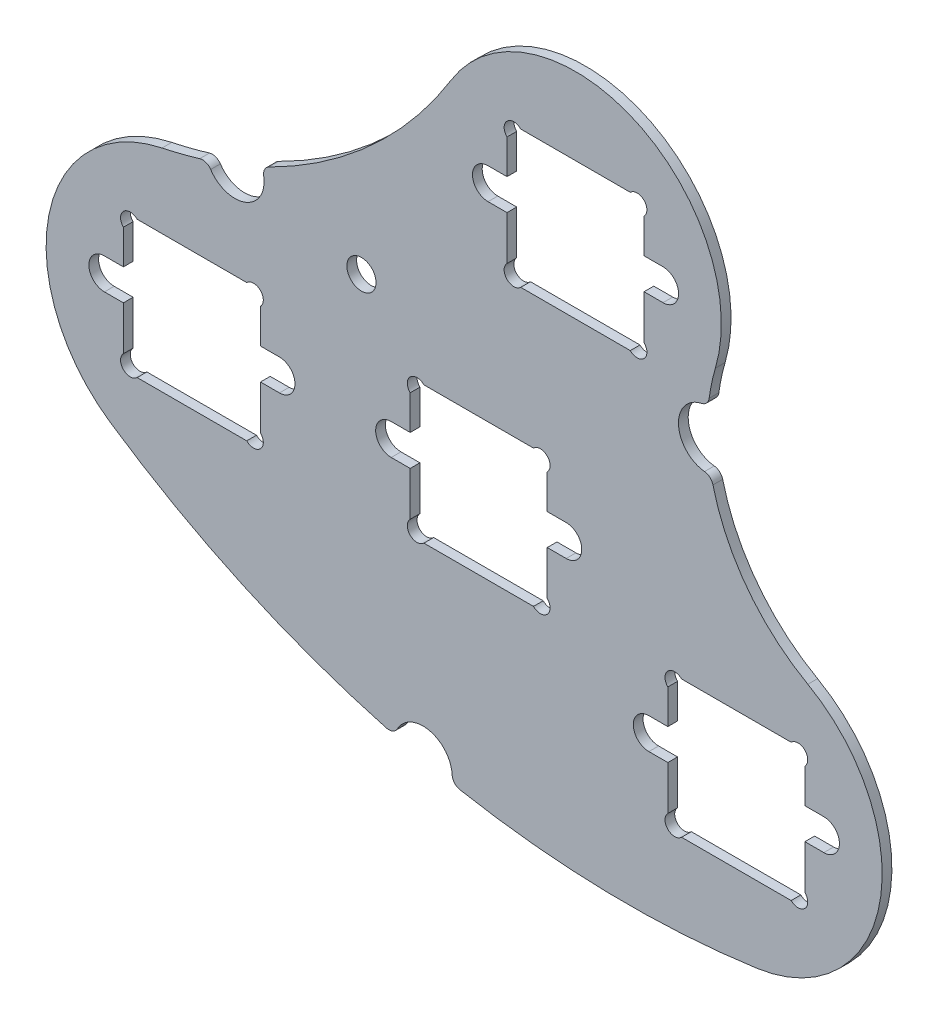
SolidWorks part; units mm, degrees
ref_plane "Front Plane" through (0, 0, 0) normal (0, 0, 1) x (1, 0, 0)
ref_plane "Top Plane" through (0, 0, 0) normal (0, 1, 0) x (1, 0, 0)
ref_plane "Right Plane" through (0, 0, 0) normal (1, 0, 0) x (0, 0, -1)
sketch "Sketch1" plane through (0, 0, 0) normal (0, 0, 1) x (1, 0, 0)
  line L0 (157.8919, 26.2701) -> (191.7747, 29.0915)
  line L1 (157.8919, 26.2701) -> (191.7747, 26.2701)
  line L2 (157.8919, 26.2701) -> (157.8919, 29.0915)
  line L3 (157.8919, 29.0915) -> (191.7747, 29.0915)
  line L4 (191.7747, 26.2701) -> (191.7747, 29.0915)
  line L5 (123.8919, 26.2701) -> (90.0092, 26.2701)
  line L6 (123.8919, 26.2701) -> (123.8919, 29.0915)
  line L7 (123.8919, 29.0915) -> (90.0092, 29.0915)
  line L8 (90.0092, 26.2701) -> (90.0092, 29.0915)
  line L9 (90.0092, 29.0915) -> (123.8919, 26.2701)
  line L10 (168.0919, 58.3601) -> (194.8735, 70.7292)
  line L11 (168.0919, 58.3601) -> (194.8735, 58.3601)
  line L12 (168.0919, 58.3601) -> (168.0919, 70.7292)
  line L13 (168.0919, 70.7292) -> (194.8735, 70.7292)
  line L14 (194.8735, 58.3601) -> (194.8735, 70.7292)
  line L15 (194.8735, 70.7292) -> (224.3587, 70.7292)
  line L16 (194.8735, 70.7292) -> (194.8735, 69.7923)
  line L17 (194.8735, 69.7923) -> (224.3587, 69.7923)
  line L18 (224.3587, 70.7292) -> (224.3587, 69.7923)
  line L19 (224.3587, 69.7923) -> (253.5106, 69.7923)
  line L20 (224.3587, 69.7923) -> (224.3587, 65.2742)
  line L21 (224.3587, 65.2742) -> (253.5106, 65.2742)
  line L22 (253.5106, 69.7923) -> (253.5106, 65.2742)
  line L23 (224.3587, 69.7923) -> (194.8735, 70.7292)
  line L24 (253.5106, 65.2742) -> (224.3587, 69.7923)
  line L25 (170.7502, 87.7401) -> (168.0919, 58.3601)
  line L26 (168.0919, 58.3601) -> (170.7502, 58.3601)
  line L27 (168.0919, 58.3601) -> (168.0919, 87.7401)
  line L28 (168.0919, 87.7401) -> (170.7502, 87.7401)
  line L29 (170.7502, 58.3601) -> (170.7502, 87.7401)
  line L30 (52.9966, 89.4705) -> (24.4119, 82.1791)
  line L31 (24.4119, 82.1791) -> (52.9966, 82.1791)
  line L32 (24.4119, 82.1791) -> (24.4119, 89.4705)
  line L33 (24.4119, 89.4705) -> (52.9966, 89.4705)
  line L34 (52.9966, 82.1791) -> (52.9966, 89.4705)
  line L35 (82.4966, 89.4705) -> (109.0019, 89.4705)
  line L36 (82.4966, 89.4705) -> (82.4966, 76.5201)
  line L37 (82.4966, 76.5201) -> (109.0019, 76.5201)
  line L38 (109.0019, 89.4705) -> (109.0019, 76.5201)
  line L39 (92.4554, 117.2387) -> (82.4966, 117.2387)
  line L40 (92.4554, 117.2387) -> (92.4554, 89.4705)
  line L41 (92.4554, 89.4705) -> (82.4966, 89.4705)
  line L42 (82.4966, 117.2387) -> (82.4966, 89.4705)
  line L43 (92.4554, 117.2387) -> (82.4966, 89.4705)
  line L44 (109.0019, 76.5201) -> (82.4966, 89.4705)
  circle A0 centre (123.8919, 26.2701) radius 14.25
  circle A1 centre (157.8919, 26.2701) radius 14.25
  circle A2 centre (90.0092, 29.0915) radius 14.25
  circle A3 centre (191.7747, 29.0915) radius 14.25
  circle A4 centre (82.4966, 89.4705) radius 11.25
  circle A5 centre (92.4554, 117.2387) radius 11.25
  circle A6 centre (52.9966, 89.4705) radius 11.25
  circle A7 centre (109.0019, 76.5201) radius 11.25
  circle A8 centre (24.4119, 82.1791) radius 11.25
  circle A9 centre (170.7502, 87.7401) radius 11.25
  circle A10 centre (168.0919, 58.3601) radius 11.25
  circle A11 centre (197.5318, 100.1092) radius 11.25
  circle A12 centre (194.8735, 70.7292) radius 11.25
  circle A13 centre (227.0169, 99.1723) radius 11.25
  circle A14 centre (224.3587, 69.7923) radius 11.25
  circle A15 centre (256.1689, 94.6541) radius 11.25
  circle A16 centre (253.5106, 65.2742) radius 11.25
  circle A17 centre (24.4119, 82.1791) radius 12
  circle A18 centre (52.9966, 89.4705) radius 12
  circle A19 centre (92.4554, 117.2387) radius 12
  circle A20 centre (82.4966, 89.4705) radius 12
  circle A21 centre (109.0019, 76.5201) radius 12
  circle A22 centre (168.0919, 58.3601) radius 12
  circle A23 centre (194.8735, 70.7292) radius 12
  circle A24 centre (224.3587, 69.7923) radius 12
  circle A25 centre (253.5106, 65.2742) radius 12
  circle A26 centre (256.1689, 94.6541) radius 12
  circle A27 centre (227.0169, 99.1723) radius 12
  circle A28 centre (197.5318, 100.1092) radius 12
  circle A29 centre (170.7502, 87.7401) radius 12
  circle A30 centre (191.7747, 29.0915) radius 15
  circle A31 centre (157.8919, 26.2701) radius 15
  circle A32 centre (123.8919, 26.2701) radius 15
  circle A33 centre (90.0092, 29.0915) radius 15
  circle A34 centre (173.429, 117.1182) radius 11.25
  circle A35 centre (173.429, 117.1182) radius 12
  dimension "D1" = 28.5
  dimension "D2" = 22.5
  dimension "D3" = 0.75
  dimension "D4" = 0.75
  dimension "D34" = 34
  dimension "D5" = 29.5
  dimension "D6" = 29.5
  dimension "D7" = 29.5
  dimension "D8" = 29.5
  dimension "D9" = 29.5
  dimension "D10" = 29.5
  dimension "D11" = 29.5
  dimension "D12" = 29.5
  dimension "D13" = 29.5
  dimension "D14" = 29.5
  dimension "D15" = 29.5
  dimension "D16" = 29.5
  dimension "D17" = 29.5
  dimension "D18" = 29.5
  dimension "D19" = 34
  dimension "D20" = 34
  dimension "D21" = 32.09
  dimension "D22" = 10.2
  dimension "D23" = 4.76
  dimension "D24" = 4.76
  dimension "D25" = 24.79
  dimension "D26" = 1.82
  dimension "D27" = 8.81
  dimension "D28" = 84.83
  dimension "D29" = 75.69
  dimension "D30" = 70.27
  dimension "D31" = 26.04
  dimension "D32" = 14.89
  dimension "D33" = 50.25
  dimension "D35" = 29.5
  dimension "D36" = 29.5
sketch "Sketch4" plane through (-30.2083, 20.075, 0) normal (0, 0, 1) x (0.9781, -0.2079, 0)
  line L0 (86.1706, 94.1917) -> (105.2206, 75.1417)
  line L1 (67.1206, 94.1917) -> (86.1706, 94.1917)
  line L2 (67.1206, 94.1917) -> (67.1206, 75.1417)
  line L3 (67.1206, 75.1417) -> (86.1706, 75.1417)
  line L4 (86.1706, 94.1917) -> (86.1706, 75.1417)
  line L5 (86.1706, 94.1917) -> (105.2206, 94.1917)
  line L6 (86.1706, 94.1917) -> (86.1706, 75.1417)
  line L7 (86.1706, 75.1417) -> (105.2206, 75.1417)
  line L8 (105.2206, 94.1917) -> (105.2206, 75.1417)
  line L9 (105.2206, 94.1917) -> (124.2706, 94.1917)
  line L10 (105.2206, 94.1917) -> (105.2206, 75.1417)
  line L11 (105.2206, 75.1417) -> (124.2706, 75.1417)
  line L12 (124.2706, 94.1917) -> (124.2706, 75.1417)
  line L13 (86.1706, 94.1917) -> (105.2206, 94.1917)
  line L14 (86.1706, 94.1917) -> (86.1706, 113.2417)
  line L15 (86.1706, 113.2417) -> (105.2206, 113.2417)
  line L16 (105.2206, 94.1917) -> (105.2206, 113.2417)
  line L17 (66.9585, 85.1784) -> (124.4326, 84.1551)
  point P14 (95.6956, 84.6667)
  point P15 (95.6956, 84.6667)
  dimension "D1" = 19.05
sketch "Sketch9" plane through (0, 0, 0) normal (0, 0, 1) x (1, 0, 0)
  line L1 (17.3619, 89.2291) -> (31.4619, 89.2291)
  line L2 (17.3619, 89.2291) -> (17.3619, 75.1291)
  line L3 (17.3619, 75.1291) -> (31.4619, 75.1291)
  line L4 (31.4619, 89.2291) -> (31.4619, 75.1291)
  line L5 (45.9466, 96.5205) -> (60.0466, 96.5205)
  line L6 (45.9466, 96.5205) -> (45.9466, 82.4205)
  line L7 (45.9466, 82.4205) -> (60.0466, 82.4205)
  line L8 (60.0466, 96.5205) -> (60.0466, 82.4205)
  line L9 (75.4466, 96.5205) -> (89.5466, 96.5205)
  line L10 (75.4466, 96.5205) -> (75.4466, 82.4205)
  line L11 (75.4466, 82.4205) -> (89.5466, 82.4205)
  line L12 (89.5466, 96.5205) -> (89.5466, 82.4205)
  line L13 (101.9519, 83.5701) -> (116.0519, 83.5701)
  line L14 (101.9519, 83.5701) -> (101.9519, 69.4701)
  line L15 (101.9519, 69.4701) -> (116.0519, 69.4701)
  line L16 (116.0519, 83.5701) -> (116.0519, 69.4701)
  line L17 (85.4054, 124.2887) -> (99.5054, 124.2887)
  line L18 (85.4054, 124.2887) -> (85.4054, 110.1887)
  line L19 (85.4054, 110.1887) -> (99.5054, 110.1887)
  line L20 (99.5054, 124.2887) -> (99.5054, 110.1887)
  line L21 (82.9592, 36.1415) -> (97.0592, 36.1415)
  line L22 (82.9592, 36.1415) -> (82.9592, 22.0415)
  line L23 (82.9592, 22.0415) -> (97.0592, 22.0415)
  line L24 (97.0592, 36.1415) -> (97.0592, 22.0415)
  line L25 (116.8419, 33.3201) -> (130.9419, 33.3201)
  line L26 (116.8419, 33.3201) -> (116.8419, 19.2201)
  line L27 (116.8419, 19.2201) -> (130.9419, 19.2201)
  line L28 (130.9419, 33.3201) -> (130.9419, 19.2201)
  line L29 (150.8419, 33.3201) -> (164.9419, 33.3201)
  line L30 (150.8419, 33.3201) -> (150.8419, 19.2201)
  line L31 (150.8419, 19.2201) -> (164.9419, 19.2201)
  line L32 (164.9419, 33.3201) -> (164.9419, 19.2201)
  line L33 (184.7247, 36.1415) -> (198.8247, 36.1415)
  line L34 (184.7247, 36.1415) -> (184.7247, 22.0415)
  line L35 (184.7247, 22.0415) -> (198.8247, 22.0415)
  line L36 (198.8247, 36.1415) -> (198.8247, 22.0415)
  line L37 (260.5606, 58.2242) -> (246.4606, 58.2242)
  line L38 (260.5606, 58.2242) -> (260.5606, 72.3242)
  line L39 (260.5606, 72.3242) -> (246.4606, 72.3242)
  line L40 (246.4606, 58.2242) -> (246.4606, 72.3242)
  line L41 (217.3087, 76.8423) -> (231.4087, 76.8423)
  line L42 (217.3087, 76.8423) -> (217.3087, 62.7423)
  line L43 (217.3087, 62.7423) -> (231.4087, 62.7423)
  line L44 (231.4087, 76.8423) -> (231.4087, 62.7423)
  line L45 (187.8235, 77.7792) -> (201.9235, 77.7792)
  line L46 (187.8235, 77.7792) -> (187.8235, 63.6792)
  line L47 (187.8235, 63.6792) -> (201.9235, 63.6792)
  line L48 (201.9235, 77.7792) -> (201.9235, 63.6792)
  line L49 (161.0419, 65.4101) -> (175.1419, 65.4101)
  line L50 (161.0419, 65.4101) -> (161.0419, 51.3101)
  line L51 (161.0419, 51.3101) -> (175.1419, 51.3101)
  line L52 (175.1419, 65.4101) -> (175.1419, 51.3101)
  line L53 (163.7002, 94.7901) -> (177.8002, 94.7901)
  line L54 (163.7002, 94.7901) -> (163.7002, 80.6901)
  line L55 (163.7002, 80.6901) -> (177.8002, 80.6901)
  line L56 (177.8002, 94.7901) -> (177.8002, 80.6901)
  line L57 (190.4818, 107.1592) -> (204.5818, 107.1592)
  line L58 (190.4818, 107.1592) -> (190.4818, 93.0592)
  line L59 (190.4818, 93.0592) -> (204.5818, 93.0592)
  line L60 (204.5818, 107.1592) -> (204.5818, 93.0592)
  line L61 (219.9669, 106.2223) -> (234.0669, 106.2223)
  line L62 (219.9669, 106.2223) -> (219.9669, 92.1223)
  line L63 (219.9669, 92.1223) -> (234.0669, 92.1223)
  line L64 (234.0669, 106.2223) -> (234.0669, 92.1223)
  line L65 (249.1189, 101.7041) -> (263.2189, 101.7041)
  line L66 (249.1189, 101.7041) -> (249.1189, 87.6041)
  line L67 (249.1189, 87.6041) -> (263.2189, 87.6041)
  line L68 (263.2189, 101.7041) -> (263.2189, 87.6041)
  line L69 (166.379, 124.1682) -> (180.479, 124.1682)
  line L70 (166.379, 124.1682) -> (166.379, 110.0682)
  line L71 (166.379, 110.0682) -> (180.479, 110.0682)
  line L72 (180.479, 124.1682) -> (180.479, 110.0682)
  point P72 (24.4119, 89.2291)
  point P74 (52.9966, 96.5205)
  point P76 (82.4966, 96.5205)
  point P78 (92.4554, 124.2887)
  point P80 (109.0019, 83.5701)
  point P82 (90.0092, 36.1415)
  point P84 (123.8919, 33.3201)
  point P86 (157.8919, 33.3201)
  point P88 (191.7747, 36.1415)
  point P90 (168.0919, 65.4101)
  point P92 (170.7502, 94.7901)
  point P94 (173.429, 124.1682)
  point P96 (197.5318, 107.1592)
  point P98 (227.0169, 106.2223)
  point P100 (256.1689, 101.7041)
  point P102 (194.8735, 77.7792)
  point P104 (224.3587, 76.8423)
  point P106 (253.5106, 72.3242)
  point P108 (17.3619, 82.1791)
  point P109 (45.9466, 89.4705)
  point P110 (75.4466, 89.4705)
  point P111 (101.9519, 76.5201)
  point P112 (85.4054, 117.2387)
  point P113 (82.9592, 29.0915)
  point P114 (116.8419, 26.2701)
  point P115 (150.8419, 26.2701)
  point P116 (184.7247, 29.0915)
  point P118 (161.0419, 58.3601)
  point P119 (187.8235, 70.7292)
  point P120 (217.3087, 69.7923)
  point P121 (246.4606, 65.2742)
  point P122 (163.7002, 87.7401)
  point P123 (190.4818, 100.1092)
  point P124 (219.9669, 99.1723)
  point P125 (249.1189, 94.6541)
  point P126 (166.379, 117.1182)
  dimension "D1" = 14.1
sketch "Sketch10" plane through (-22.0981, 19.3454, 0) normal (0, 0, 1) x (0.9781, -0.2079, 0)
  line L1 (61.5108, 90.7441) -> (75.6108, 90.7441)
  line L2 (61.5108, 90.7441) -> (61.5108, 76.6441)
  line L3 (61.5108, 76.6441) -> (75.6108, 76.6441)
  line L4 (75.6108, 90.7441) -> (75.6108, 76.6441)
  line L5 (80.5608, 90.7441) -> (94.6608, 90.7441)
  line L6 (80.5608, 90.7441) -> (80.5608, 76.6441)
  line L7 (80.5608, 76.6441) -> (94.6608, 76.6441)
  line L8 (94.6608, 90.7441) -> (94.6608, 76.6441)
  line L9 (99.6108, 90.7441) -> (113.7108, 90.7441)
  line L10 (99.6108, 90.7441) -> (99.6108, 76.6441)
  line L11 (99.6108, 76.6441) -> (113.7108, 76.6441)
  line L12 (113.7108, 90.7441) -> (113.7108, 76.6441)
  line L13 (80.5608, 109.7941) -> (94.6608, 109.7941)
  line L14 (80.5608, 109.7941) -> (80.5608, 95.6941)
  line L15 (80.5608, 95.6941) -> (94.6608, 95.6941)
  line L16 (94.6608, 109.7941) -> (94.6608, 95.6941)
  line L17 (50.5121, 89.6359) -> (53.4436, 75.8441) construction
  line L18 (59.0358, 93.2191) -> (78.0858, 93.2191) construction
  line L19 (78.0858, 112.2691) -> (97.1358, 112.2691) construction
  line L20 (97.1358, 93.2191) -> (116.1858, 93.2191) construction
  line L21 (78.0858, 93.2191) -> (78.0858, 112.2691) construction
  line L23 (59.0358, 93.2191) -> (59.0358, 74.1691) construction
  point P16 (75.6108, 83.6941)
  point P17 (94.6608, 83.6941)
  point P18 (113.7108, 83.6941)
  point P19 (87.6108, 90.7441)
  point P20 (87.6108, 109.7941)
  point P23 (68.5608, 90.7441)
  point P26 (68.5608, 93.2191)
  point P29 (87.6108, 112.2691)
  point P30 (106.6608, 90.7441)
  point P33 (106.6608, 93.2191)
  point P34 (80.5608, 102.7441)
  point P37 (78.0858, 102.7441)
  point P42 (59.0358, 83.6941)
  point P43 (61.5108, 83.6941)
sketch "Sketch14" plane through (0, 0, 0) normal (0, 0, 1) x (1, 0, 0)
  line L0 (165.1144, 80.6901) -> (163.7002, 82.1043)
  line L1 (163.7002, 93.3758) -> (165.1144, 94.7901)
  line L2 (177.8002, 93.3758) -> (176.386, 94.7901)
  line L3 (179.0648, 110.0682) -> (180.479, 111.4824)
  line L4 (166.379, 111.4824) -> (167.7932, 110.0682)
  line L5 (166.379, 122.754) -> (167.7932, 124.1682)
  line L6 (179.0648, 124.1682) -> (180.479, 122.754)
  line L7 (203.1676, 93.0592) -> (204.5818, 94.4734)
  line L8 (17.3619, 89.2291) -> (17.3619, 75.1291) construction
  line L9 (17.3619, 89.2291) -> (31.4619, 89.2291) construction
  line L10 (17.3619, 87.8149) -> (18.7761, 89.2291)
  line L11 (17.3619, 75.1291) -> (31.4619, 75.1291) construction
  line L12 (31.4619, 89.2291) -> (31.4619, 75.1291) construction
  line L13 (45.9466, 96.5205) -> (60.0466, 96.5205) construction
  line L14 (60.0466, 96.5205) -> (60.0466, 82.4205) construction
  line L15 (45.9466, 96.5205) -> (45.9466, 82.4205) construction
  line L16 (45.9466, 82.4205) -> (60.0466, 82.4205) construction
  line L17 (85.4054, 124.2887) -> (85.4054, 110.1887) construction
  line L18 (85.4054, 124.2887) -> (99.5054, 124.2887) construction
  line L19 (99.5054, 124.2887) -> (99.5054, 110.1887) construction
  line L20 (85.4054, 110.1887) -> (99.5054, 110.1887) construction
  line L21 (101.9519, 83.5701) -> (101.9519, 69.4701) construction
  line L22 (101.9519, 83.5701) -> (116.0519, 83.5701) construction
  line L23 (116.0519, 83.5701) -> (116.0519, 69.4701) construction
  line L24 (101.9519, 69.4701) -> (116.0519, 69.4701) construction
  line L25 (91.2712, 73.6044) -> (105.0631, 70.6729) construction
  line L26 (107.9947, 84.4647) -> (105.0631, 70.6729) construction
  line L27 (94.2028, 87.3963) -> (107.9947, 84.4647) construction
  line L28 (94.2028, 87.3963) -> (91.2712, 73.6044) construction
  line L29 (72.6375, 77.5651) -> (86.4294, 74.6336) construction
  line L30 (89.361, 88.4255) -> (86.4294, 74.6336) construction
  line L31 (75.5691, 91.357) -> (89.361, 88.4255) construction
  line L32 (75.5691, 91.357) -> (72.6375, 77.5651) construction
  line L33 (56.9354, 95.3177) -> (54.0038, 81.5259) construction
  line L34 (56.9354, 95.3177) -> (70.7273, 92.3862) construction
  line L35 (70.7273, 92.3862) -> (67.7957, 78.5943) construction
  line L36 (54.0038, 81.5259) -> (67.7957, 78.5943) construction
  line L37 (76.5983, 96.1988) -> (90.3901, 93.2673) construction
  line L38 (93.3217, 107.0592) -> (90.3901, 93.2673) construction
  line L39 (79.5298, 109.9907) -> (76.5983, 96.1988) construction
  line L40 (79.5298, 109.9907) -> (93.3217, 107.0592) construction
  line L41 (82.9592, 36.1415) -> (82.9592, 22.0415) construction
  line L42 (82.9592, 36.1415) -> (97.0592, 36.1415) construction
  line L43 (82.9592, 22.0415) -> (97.0592, 22.0415) construction
  line L44 (97.0592, 36.1415) -> (97.0592, 22.0415) construction
  line L45 (116.8419, 33.3201) -> (116.8419, 19.2201) construction
  line L46 (116.8419, 33.3201) -> (130.9419, 33.3201) construction
  line L47 (116.8419, 19.2201) -> (130.9419, 19.2201) construction
  line L48 (130.9419, 33.3201) -> (130.9419, 19.2201) construction
  line L49 (150.8419, 33.3201) -> (150.8419, 19.2201) construction
  line L50 (150.8419, 33.3201) -> (164.9419, 33.3201) construction
  line L51 (164.9419, 33.3201) -> (164.9419, 19.2201) construction
  line L52 (150.8419, 19.2201) -> (164.9419, 19.2201) construction
  line L53 (184.7247, 36.1415) -> (184.7247, 22.0415) construction
  line L54 (184.7247, 22.0415) -> (198.8247, 22.0415) construction
  line L55 (198.8247, 36.1415) -> (198.8247, 22.0415) construction
  line L56 (184.7247, 36.1415) -> (198.8247, 36.1415) construction
  line L57 (161.0419, 65.4101) -> (175.1419, 65.4101) construction
  line L58 (175.1419, 65.4101) -> (175.1419, 51.3101) construction
  line L59 (161.0419, 51.3101) -> (175.1419, 51.3101) construction
  line L60 (161.0419, 65.4101) -> (161.0419, 51.3101) construction
  line L61 (187.8235, 77.7792) -> (187.8235, 63.6792) construction
  line L62 (187.8235, 77.7792) -> (201.9235, 77.7792) construction
  line L63 (187.8235, 63.6792) -> (201.9235, 63.6792) construction
  line L64 (201.9235, 77.7792) -> (201.9235, 63.6792) construction
  line L65 (217.3087, 76.8423) -> (217.3087, 62.7423) construction
  line L66 (217.3087, 76.8423) -> (231.4087, 76.8423) construction
  line L67 (231.4087, 76.8423) -> (231.4087, 62.7423) construction
  line L68 (217.3087, 62.7423) -> (231.4087, 62.7423) construction
  line L69 (260.5606, 58.2242) -> (246.4606, 58.2242) construction
  line L70 (260.5606, 58.2242) -> (260.5606, 72.3242) construction
  line L71 (246.4606, 58.2242) -> (246.4606, 72.3242) construction
  line L72 (260.5606, 72.3242) -> (246.4606, 72.3242) construction
  line L73 (249.1189, 101.7041) -> (263.2189, 101.7041) construction
  line L74 (263.2189, 101.7041) -> (263.2189, 87.6041) construction
  line L75 (249.1189, 87.6041) -> (263.2189, 87.6041) construction
  line L76 (249.1189, 101.7041) -> (249.1189, 87.6041) construction
  line L77 (219.9669, 106.2223) -> (219.9669, 92.1223) construction
  line L78 (219.9669, 106.2223) -> (234.0669, 106.2223) construction
  line L79 (234.0669, 106.2223) -> (234.0669, 92.1223) construction
  line L80 (219.9669, 92.1223) -> (234.0669, 92.1223) construction
  line L81 (190.4818, 107.1592) -> (204.5818, 107.1592) construction
  line L82 (204.5818, 107.1592) -> (204.5818, 93.0592) construction
  line L83 (190.4818, 93.0592) -> (204.5818, 93.0592) construction
  line L84 (190.4818, 107.1592) -> (190.4818, 93.0592) construction
  line L85 (163.7002, 94.7901) -> (177.8002, 94.7901) construction
  line L86 (177.8002, 94.7901) -> (177.8002, 80.6901) construction
  line L87 (163.7002, 80.6901) -> (177.8002, 80.6901) construction
  line L88 (163.7002, 94.7901) -> (163.7002, 80.6901) construction
  line L89 (180.479, 124.1682) -> (180.479, 110.0682) construction
  line L90 (166.379, 110.0682) -> (180.479, 110.0682) construction
  line L91 (166.379, 124.1682) -> (166.379, 110.0682) construction
  line L92 (166.379, 124.1682) -> (180.479, 124.1682) construction
  line L93 (17.3619, 76.5433) -> (18.7761, 75.1291)
  line L94 (30.0477, 75.1291) -> (31.4619, 76.5433)
  line L95 (31.4619, 87.8149) -> (30.0477, 89.2291)
  line L96 (45.9466, 95.1063) -> (47.3608, 96.5205)
  line L97 (45.9466, 83.8347) -> (47.3608, 82.4205)
  line L98 (54.2979, 82.9092) -> (55.3871, 81.2318)
  line L99 (58.6323, 82.4205) -> (60.0466, 83.8347)
  line L100 (56.6413, 93.9344) -> (58.3187, 95.0237)
  line L101 (58.6323, 96.5205) -> (60.0466, 95.1063)
  line L102 (69.3439, 92.6802) -> (70.4332, 91.0029)
  line L103 (68.0897, 79.9776) -> (66.4124, 78.8883)
  line L104 (75.2751, 89.9737) -> (76.9524, 91.063)
  line L105 (72.9316, 78.9484) -> (74.0208, 77.2711)
  line L106 (85.0461, 74.9276) -> (86.7234, 76.0169)
  line L107 (89.0669, 87.0421) -> (87.9777, 88.7195)
  line L108 (89.0068, 93.5613) -> (90.6842, 94.6506)
  line L109 (76.8923, 97.5822) -> (77.9816, 95.9048)
  line L110 (91.9384, 107.3532) -> (93.0277, 105.6759)
  line L111 (79.2358, 108.6074) -> (80.9131, 109.6967)
  line L112 (85.4054, 111.6029) -> (86.8196, 110.1887)
  line L113 (98.0912, 110.1887) -> (99.5054, 111.6029)
  line L114 (98.0912, 124.2887) -> (99.5054, 122.8745)
  line L115 (85.4054, 122.8745) -> (86.8196, 124.2887)
  line L116 (93.9088, 86.013) -> (95.5861, 87.1023)
  line L117 (91.5653, 74.9877) -> (92.6546, 73.3104)
  line L118 (103.6798, 70.9669) -> (105.3572, 72.0562)
  line L119 (106.6114, 84.7588) -> (107.7006, 83.0814)
  line L120 (101.9519, 82.1559) -> (103.3662, 83.5701)
  line L121 (101.9519, 70.8843) -> (103.3662, 69.4701)
  line L122 (114.6377, 69.4701) -> (116.0519, 70.8843)
  line L123 (116.0519, 82.1559) -> (114.6377, 83.5701)
  line L124 (82.9592, 34.7272) -> (84.3734, 36.1415)
  line L125 (82.9592, 23.4557) -> (84.3734, 22.0415)
  line L126 (95.645, 22.0415) -> (97.0592, 23.4557)
  line L127 (97.0592, 34.7272) -> (95.645, 36.1415)
  line L128 (116.8419, 31.9059) -> (118.2562, 33.3201)
  line L129 (116.8419, 20.6343) -> (118.2562, 19.2201)
  line L130 (129.5277, 19.2201) -> (130.9419, 20.6343)
  line L131 (130.9419, 31.9059) -> (129.5277, 33.3201)
  line L132 (150.8419, 31.9059) -> (152.2562, 33.3201)
  line L133 (150.8419, 20.6343) -> (152.2562, 19.2201)
  line L134 (163.5277, 19.2201) -> (164.9419, 20.6343)
  line L135 (164.9419, 31.9059) -> (163.5277, 33.3201)
  line L136 (184.7247, 34.7272) -> (186.1389, 36.1415)
  line L137 (184.7247, 23.4557) -> (186.1389, 22.0415)
  line L138 (197.4105, 22.0415) -> (198.8247, 23.4557)
  line L139 (198.8247, 34.7272) -> (197.4105, 36.1415)
  line L140 (173.7277, 51.3101) -> (175.1419, 52.7243)
  line L141 (161.0419, 52.7243) -> (162.4562, 51.3101)
  line L142 (161.0419, 63.9959) -> (162.4562, 65.4101)
  line L143 (173.7277, 65.4101) -> (175.1419, 63.9959)
  line L144 (187.8235, 65.0934) -> (189.2378, 63.6792)
  line L145 (200.5093, 63.6792) -> (201.9235, 65.0934)
  line L146 (200.5093, 77.7792) -> (201.9235, 76.365)
  line L147 (187.8235, 76.365) -> (189.2378, 77.7792)
  line L148 (176.386, 80.6901) -> (177.8002, 82.1043)
  line L149 (204.5818, 105.745) -> (203.1676, 107.1592)
  line L150 (191.896, 107.1592) -> (190.4818, 105.745)
  line L151 (190.4818, 94.4734) -> (191.896, 93.0592)
  line L152 (219.9669, 104.8081) -> (221.3812, 106.2223)
  line L153 (232.6527, 106.2223) -> (234.0669, 104.8081)
  line L154 (234.0669, 93.5365) -> (232.6527, 92.1223)
  line L155 (219.9669, 93.5365) -> (221.3812, 92.1223)
  line L156 (229.9944, 76.8423) -> (231.4087, 75.4281)
  line L157 (217.3087, 75.4281) -> (218.7229, 76.8423)
  line L158 (217.3087, 64.1565) -> (218.7229, 62.7423)
  line L159 (229.9944, 62.7423) -> (231.4087, 64.1565)
  line L160 (259.1464, 72.3242) -> (260.5606, 70.9099)
  line L161 (246.4606, 70.9099) -> (247.8748, 72.3242)
  line L162 (259.1464, 58.2242) -> (260.5606, 59.6384)
  line L163 (247.8748, 58.2242) -> (246.4606, 59.6384)
  line L164 (261.8047, 87.6041) -> (263.2189, 89.0183)
  line L165 (249.1189, 89.0183) -> (250.5331, 87.6041)
  line L166 (249.1189, 100.2899) -> (250.5331, 101.7041)
  line L167 (261.8047, 101.7041) -> (263.2189, 100.2899)
  line L168 (75.4466, 96.5205) -> (75.4466, 82.4205) construction
  line L169 (75.4466, 96.5205) -> (89.5466, 96.5205) construction
  line L170 (89.5466, 96.5205) -> (89.5466, 82.4205) construction
  line L171 (75.4466, 82.4205) -> (89.5466, 82.4205) construction
  line L172 (76.8608, 96.5205) -> (75.4466, 95.1063)
  line L173 (88.1323, 96.5205) -> (89.5466, 95.1063)
  line L174 (89.5466, 83.8347) -> (88.1323, 82.4205)
  line L175 (75.4466, 83.8347) -> (76.8608, 82.4205)
  arc A0 (17.3619, 87.8149) -> (18.7761, 89.2291) centre (18.069, 88.522) cw
  arc A1 (18.7761, 75.1291) -> (17.3619, 76.5433) centre (18.069, 75.8362) cw
  arc A2 (31.4619, 76.5433) -> (30.0477, 75.1291) centre (30.7548, 75.8362) cw
  arc A3 (30.0477, 89.2291) -> (31.4619, 87.8149) centre (30.7548, 88.522) cw
  arc A4 (58.6323, 96.5205) -> (60.0466, 95.1063) centre (59.3394, 95.8134) cw
  arc A5 (45.9466, 95.1063) -> (47.3608, 96.5205) centre (46.6537, 95.8134) cw
  arc A6 (47.3608, 82.4205) -> (45.9466, 83.8347) centre (46.6537, 83.1276) cw
  arc A7 (60.0466, 83.8347) -> (58.6323, 82.4205) centre (59.3394, 83.1276) cw
  arc A8 (85.4054, 122.8745) -> (86.8196, 124.2887) centre (86.1125, 123.5816) cw
  arc A9 (98.0912, 124.2887) -> (99.5054, 122.8745) centre (98.7983, 123.5816) cw
  arc A10 (99.5054, 111.6029) -> (98.0912, 110.1887) centre (98.7983, 110.8958) cw
  arc A11 (85.4054, 111.6029) -> (86.8196, 110.1887) centre (86.1125, 110.8958) ccw
  arc A12 (101.9519, 82.1559) -> (103.3662, 83.5701) centre (102.6591, 82.863) cw
  arc A13 (114.6377, 83.5701) -> (116.0519, 82.1559) centre (115.3448, 82.863) cw
  arc A14 (116.0519, 70.8843) -> (114.6377, 69.4701) centre (115.3448, 70.1772) cw
  arc A15 (101.9519, 70.8843) -> (103.3662, 69.4701) centre (102.6591, 70.1772) ccw
  arc A16 (103.6798, 70.9669) -> (105.3572, 72.0562) centre (104.5185, 71.5115) ccw
  arc A17 (106.6114, 84.7588) -> (107.7006, 83.0814) centre (107.156, 83.9201) cw
  arc A18 (93.9088, 86.013) -> (95.5861, 87.1023) centre (94.7474, 86.5576) cw
  arc A19 (91.5653, 74.9877) -> (92.6546, 73.3104) centre (92.1099, 74.1491) ccw
  arc A20 (85.0461, 74.9276) -> (86.7234, 76.0169) centre (85.8848, 75.4722) ccw
  arc A21 (87.9777, 88.7195) -> (89.0669, 87.0421) centre (88.5223, 87.8808) cw
  arc A22 (75.2751, 89.9737) -> (76.9524, 91.063) centre (76.1137, 90.5183) cw
  arc A23 (72.9316, 78.9484) -> (74.0208, 77.2711) centre (73.4762, 78.1098) ccw
  arc A24 (56.6413, 93.9344) -> (58.3187, 95.0237) centre (57.48, 94.4791) cw
  arc A25 (69.3439, 92.6802) -> (70.4332, 91.0029) centre (69.8886, 91.8415) cw
  arc A26 (68.0897, 79.9776) -> (66.4124, 78.8883) centre (67.2511, 79.433) cw
  arc A27 (54.2979, 82.9092) -> (55.3871, 81.2318) centre (54.8425, 82.0705) ccw
  arc A28 (89.0068, 93.5613) -> (90.6842, 94.6506) centre (89.8455, 94.106) ccw
  arc A29 (76.8923, 97.5822) -> (77.9816, 95.9048) centre (77.4369, 96.7435) ccw
  arc A30 (79.2358, 108.6074) -> (80.9131, 109.6967) centre (80.0744, 109.1521) cw
  arc A31 (91.9384, 107.3532) -> (93.0277, 105.6759) centre (92.483, 106.5145) cw
  arc A32 (82.9592, 34.7272) -> (84.3734, 36.1415) centre (83.6663, 35.4344) cw
  arc A33 (82.9592, 23.4557) -> (84.3734, 22.0415) centre (83.6663, 22.7486) ccw
  arc A34 (95.645, 22.0415) -> (97.0592, 23.4557) centre (96.3521, 22.7486) ccw
  arc A35 (95.645, 36.1415) -> (97.0592, 34.7272) centre (96.3521, 35.4344) cw
  arc A36 (116.8419, 31.9059) -> (118.2562, 33.3201) centre (117.5491, 32.613) cw
  arc A37 (116.8419, 20.6343) -> (118.2562, 19.2201) centre (117.5491, 19.9272) ccw
  arc A38 (129.5277, 19.2201) -> (130.9419, 20.6343) centre (130.2348, 19.9272) ccw
  arc A39 (129.5277, 33.3201) -> (130.9419, 31.9059) centre (130.2348, 32.613) cw
  arc A40 (150.8419, 31.9059) -> (152.2562, 33.3201) centre (151.5491, 32.613) cw
  arc A41 (163.5277, 33.3201) -> (164.9419, 31.9059) centre (164.2348, 32.613) cw
  arc A42 (164.9419, 20.6343) -> (163.5277, 19.2201) centre (164.2348, 19.9272) cw
  arc A43 (150.8419, 20.6343) -> (152.2562, 19.2201) centre (151.5491, 19.9272) ccw
  arc A44 (184.7247, 23.4557) -> (186.1389, 22.0415) centre (185.4318, 22.7486) ccw
  arc A45 (197.4105, 22.0415) -> (198.8247, 23.4557) centre (198.1176, 22.7486) ccw
  arc A46 (197.4105, 36.1415) -> (198.8247, 34.7272) centre (198.1176, 35.4344) cw
  arc A47 (184.7247, 34.7272) -> (186.1389, 36.1415) centre (185.4318, 35.4344) cw
  arc A48 (173.7277, 65.4101) -> (175.1419, 63.9959) centre (174.4348, 64.703) cw
  arc A49 (175.1419, 52.7243) -> (173.7277, 51.3101) centre (174.4348, 52.0172) cw
  arc A50 (161.0419, 52.7243) -> (162.4562, 51.3101) centre (161.7491, 52.0172) ccw
  arc A51 (161.0419, 63.9959) -> (162.4562, 65.4101) centre (161.7491, 64.703) cw
  arc A52 (187.8235, 76.365) -> (189.2378, 77.7792) centre (188.5306, 77.0721) cw
  arc A53 (187.8235, 65.0934) -> (189.2378, 63.6792) centre (188.5306, 64.3863) ccw
  arc A54 (200.5093, 63.6792) -> (201.9235, 65.0934) centre (201.2164, 64.3863) ccw
  arc A55 (200.5093, 77.7792) -> (201.9235, 76.365) centre (201.2164, 77.0721) cw
  arc A56 (217.3087, 75.4281) -> (218.7229, 76.8423) centre (218.0158, 76.1352) cw
  arc A57 (229.9944, 76.8423) -> (231.4087, 75.4281) centre (230.7016, 76.1352) cw
  arc A58 (231.4087, 64.1565) -> (229.9944, 62.7423) centre (230.7016, 63.4494) cw
  arc A59 (217.3087, 64.1565) -> (218.7229, 62.7423) centre (218.0158, 63.4494) ccw
  arc A60 (259.1464, 58.2242) -> (260.5606, 59.6384) centre (259.8535, 58.9313) ccw
  arc A61 (246.4606, 59.6384) -> (247.8748, 58.2242) centre (247.1677, 58.9313) ccw
  arc A62 (246.4606, 70.9099) -> (247.8748, 72.3242) centre (247.1677, 71.617) cw
  arc A63 (259.1464, 72.3242) -> (260.5606, 70.9099) centre (259.8535, 71.617) cw
  arc A64 (261.8047, 101.7041) -> (263.2189, 100.2899) centre (262.5118, 100.997) cw
  arc A65 (263.2189, 89.0183) -> (261.8047, 87.6041) centre (262.5118, 88.3112) cw
  arc A66 (250.5331, 87.6041) -> (249.1189, 89.0183) centre (249.826, 88.3112) cw
  arc A67 (249.1189, 100.2899) -> (250.5331, 101.7041) centre (249.826, 100.997) cw
  arc A68 (219.9669, 104.8081) -> (221.3812, 106.2223) centre (220.674, 105.5152) cw
  arc A69 (232.6527, 106.2223) -> (234.0669, 104.8081) centre (233.3598, 105.5152) cw
  arc A70 (234.0669, 93.5365) -> (232.6527, 92.1223) centre (233.3598, 92.8294) cw
  arc A71 (221.3812, 92.1223) -> (219.9669, 93.5365) centre (220.674, 92.8294) cw
  arc A72 (203.1676, 107.1592) -> (204.5818, 105.745) centre (203.8747, 106.4521) cw
  arc A73 (204.5818, 94.4734) -> (203.1676, 93.0592) centre (203.8747, 93.7663) cw
  arc A74 (191.896, 93.0592) -> (190.4818, 94.4734) centre (191.1889, 93.7663) cw
  arc A75 (190.4818, 105.745) -> (191.896, 107.1592) centre (191.1889, 106.4521) cw
  arc A76 (176.386, 94.7901) -> (177.8002, 93.3758) centre (177.0931, 94.0829) cw
  arc A77 (177.8002, 82.1043) -> (176.386, 80.6901) centre (177.0931, 81.3972) cw
  arc A78 (165.1144, 80.6901) -> (163.7002, 82.1043) centre (164.4073, 81.3972) cw
  arc A79 (163.7002, 93.3758) -> (165.1144, 94.7901) centre (164.4073, 94.0829) cw
  arc A80 (180.479, 111.4824) -> (179.0648, 110.0682) centre (179.7719, 110.7753) cw
  arc A81 (167.7932, 110.0682) -> (166.379, 111.4824) centre (167.0861, 110.7753) cw
  arc A82 (179.0648, 124.1682) -> (180.479, 122.754) centre (179.7719, 123.4611) cw
  arc A83 (166.379, 122.754) -> (167.7932, 124.1682) centre (167.0861, 123.4611) cw
  arc A84 (75.4466, 95.1063) -> (76.8608, 96.5205) centre (76.1537, 95.8134) cw
  arc A85 (88.1323, 96.5205) -> (89.5466, 95.1063) centre (88.8394, 95.8134) cw
  arc A86 (89.5466, 83.8347) -> (88.1323, 82.4205) centre (88.8394, 83.1276) cw
  arc A87 (76.8608, 82.4205) -> (75.4466, 83.8347) centre (76.1537, 83.1276) cw
  dimension "D1" = 45
  dimension "D2" = 1
  dimension "D71" = 45
  dimension "D3" = 45
  dimension "D4" = 45
  dimension "D5" = 45
  dimension "D6" = 45
  dimension "D7" = 45
  dimension "D8" = 45
  dimension "D9" = 45
  dimension "D10" = 45
  dimension "D11" = 45
  dimension "D12" = 45
  dimension "D13" = 45
  dimension "D14" = 45
  dimension "D15" = 45
  dimension "D16" = 45
  dimension "D17" = 45
  dimension "D18" = 45
  dimension "D19" = 45
  dimension "D20" = 45
  dimension "D21" = 45
  dimension "D22" = 45
  dimension "D23" = 45
  dimension "D24" = 45
  dimension "D25" = 45
  dimension "D26" = 45
  dimension "D27" = 45
  dimension "D28" = 45
  dimension "D29" = 45
  dimension "D30" = 45
  dimension "D31" = 45
  dimension "D32" = 45
  dimension "D33" = 45
  dimension "D34" = 45
  dimension "D35" = 45
  dimension "D36" = 45
  dimension "D37" = 45
  dimension "D38" = 45
  dimension "D39" = 45
  dimension "D40" = 45
  dimension "D41" = 45
  dimension "D42" = 45
  dimension "D43" = 45
  dimension "D44" = 45
  dimension "D45" = 45
  dimension "D46" = 45
  dimension "D47" = 45
  dimension "D48" = 45
  dimension "D49" = 45
  dimension "D50" = 45
  dimension "D51" = 45
  dimension "D52" = 45
  dimension "D53" = 45
  dimension "D54" = 45
  dimension "D55" = 45
  dimension "D56" = 45
  dimension "D57" = 45
  dimension "D58" = 45
  dimension "D59" = 45
  dimension "D60" = 45
  dimension "D61" = 45
  dimension "D62" = 45
  dimension "D63" = 45
  dimension "D64" = 45
  dimension "D65" = 45
  dimension "D66" = 45
  dimension "D67" = 45
  dimension "D68" = 45
  dimension "D69" = 45
  dimension "D70" = 45
  dimension "D72" = 45
  dimension "D73" = 45
  dimension "D74" = 45
  dimension "D75" = 45
  dimension "D76" = 45
  dimension "D77" = 45
  dimension "D78" = 45
  dimension "D79" = 45
  dimension "D80" = 45
  dimension "D81" = 45
  dimension "D82" = 45
  dimension "D83" = 45
  dimension "D84" = 45
  dimension "D85" = 45
  dimension "D86" = 45
  dimension "D87" = 45
  dimension "D88" = 45
  dimension "D89" = 45
sketch "Sketch16" plane through (0, 0, 0) normal (0, 0, 1) x (1, 0, 0)
  line L0 (81.0092, 30.6915) -> (99.0092, 30.6915)
  line L5 (17.3619, 89.2291) -> (17.3619, 75.1291) construction
  line L6 (81.0092, 30.6915) -> (81.0092, 27.4915)
  line L7 (17.3619, 75.1291) -> (31.4619, 75.1291) construction
  line L8 (15.4119, 83.7791) -> (33.4119, 83.7791)
  line L9 (15.4119, 83.7791) -> (15.4119, 80.5791)
  line L10 (15.4119, 80.5791) -> (33.4119, 80.5791)
  line L11 (33.4119, 83.7791) -> (33.4119, 80.5791)
  line L12 (81.0092, 27.4915) -> (99.0092, 27.4915)
  line L13 (99.0092, 30.6915) -> (99.0092, 27.4915)
  line L14 (114.8919, 27.8701) -> (132.8919, 27.8701)
  line L15 (114.8919, 27.8701) -> (114.8919, 24.6701)
  line L16 (114.8919, 24.6701) -> (132.8919, 24.6701)
  line L17 (132.8919, 27.8701) -> (132.8919, 24.6701)
  line L18 (148.8919, 27.8701) -> (166.8919, 27.8701)
  line L19 (148.8919, 27.8701) -> (148.8919, 24.6701)
  line L20 (148.8919, 24.6701) -> (166.8919, 24.6701)
  line L21 (166.8919, 27.8701) -> (166.8919, 24.6701)
  line L22 (182.7747, 30.6915) -> (200.7747, 30.6915)
  line L23 (182.7747, 30.6915) -> (182.7747, 27.4915)
  line L24 (182.7747, 27.4915) -> (200.7747, 27.4915)
  line L25 (200.7747, 30.6915) -> (200.7747, 27.4915)
  line L26 (43.9966, 91.5705) -> (61.9966, 91.5705)
  line L27 (43.9966, 91.5705) -> (43.9966, 88.3705)
  line L28 (43.9966, 88.3705) -> (61.9966, 88.3705)
  line L29 (61.9966, 91.5705) -> (61.9966, 88.3705)
  line L30 (73.4966, 91.5705) -> (91.4966, 91.5705)
  line L31 (73.4966, 91.5705) -> (73.4966, 88.3705)
  line L32 (73.4966, 88.3705) -> (91.4966, 88.3705)
  line L33 (91.4966, 91.5705) -> (91.4966, 88.3705)
  line L34 (100.0019, 78.6201) -> (118.0019, 78.6201)
  line L35 (100.0019, 78.6201) -> (100.0019, 75.4201)
  line L36 (100.0019, 75.4201) -> (118.0019, 75.4201)
  line L37 (118.0019, 78.6201) -> (118.0019, 75.4201)
  line L38 (83.4554, 119.3387) -> (101.4554, 119.3387)
  line L39 (83.4554, 119.3387) -> (83.4554, 116.1387)
  line L40 (83.4554, 116.1387) -> (101.4554, 116.1387)
  line L41 (101.4554, 119.3387) -> (101.4554, 116.1387)
  line L42 (164.429, 118.7182) -> (182.429, 118.7182)
  line L43 (164.429, 118.7182) -> (164.429, 115.5182)
  line L44 (164.429, 115.5182) -> (182.429, 115.5182)
  line L45 (182.429, 118.7182) -> (182.429, 115.5182)
  line L46 (161.7502, 89.3401) -> (179.7502, 89.3401)
  line L47 (161.7502, 89.3401) -> (161.7502, 86.1401)
  line L48 (161.7502, 86.1401) -> (179.7502, 86.1401)
  line L49 (179.7502, 89.3401) -> (179.7502, 86.1401)
  line L50 (188.5318, 101.7092) -> (206.5318, 101.7092)
  line L51 (188.5318, 101.7092) -> (188.5318, 98.5092)
  line L52 (188.5318, 98.5092) -> (206.5318, 98.5092)
  line L53 (206.5318, 101.7092) -> (206.5318, 98.5092)
  line L54 (159.0919, 59.9601) -> (177.0919, 59.9601)
  line L55 (159.0919, 59.9601) -> (159.0919, 56.7601)
  line L56 (159.0919, 56.7601) -> (177.0919, 56.7601)
  line L57 (177.0919, 59.9601) -> (177.0919, 56.7601)
  line L58 (185.8735, 72.3292) -> (203.8735, 72.3292)
  line L59 (185.8735, 72.3292) -> (185.8735, 69.1292)
  line L60 (185.8735, 69.1292) -> (203.8735, 69.1292)
  line L61 (203.8735, 72.3292) -> (203.8735, 69.1292)
  line L62 (218.0169, 100.7723) -> (236.0169, 100.7723)
  line L63 (218.0169, 100.7723) -> (218.0169, 97.5723)
  line L64 (218.0169, 97.5723) -> (236.0169, 97.5723)
  line L65 (236.0169, 100.7723) -> (236.0169, 97.5723)
  line L66 (215.3587, 71.3923) -> (233.3587, 71.3923)
  line L67 (215.3587, 71.3923) -> (215.3587, 68.1923)
  line L68 (215.3587, 68.1923) -> (233.3587, 68.1923)
  line L69 (233.3587, 71.3923) -> (233.3587, 68.1923)
  line L70 (247.1689, 96.2541) -> (265.1689, 96.2541)
  line L71 (247.1689, 96.2541) -> (247.1689, 93.0541)
  line L72 (247.1689, 93.0541) -> (265.1689, 93.0541)
  line L73 (265.1689, 96.2541) -> (265.1689, 93.0541)
  line L74 (244.5106, 66.8742) -> (262.5106, 66.8742)
  line L75 (244.5106, 66.8742) -> (244.5106, 63.6742)
  line L76 (244.5106, 63.6742) -> (262.5106, 63.6742)
  line L77 (262.5106, 66.8742) -> (262.5106, 63.6742)
  circle A0 centre (15.4119, 82.1791) radius 1.6
  circle A1 centre (33.4119, 82.1791) radius 1.6
  circle A2 centre (81.0092, 29.0915) radius 1.6
  circle A3 centre (99.0092, 29.0915) radius 1.6
  circle A4 centre (114.8919, 26.2701) radius 1.6
  circle A5 centre (132.8919, 26.2701) radius 1.6
  circle A6 centre (148.8919, 26.2701) radius 1.6
  circle A7 centre (166.8919, 26.2701) radius 1.6
  circle A8 centre (182.7747, 29.0915) radius 1.6
  circle A9 centre (200.7747, 29.0915) radius 1.6
  circle A10 centre (43.9966, 89.9705) radius 1.6
  circle A11 centre (61.9966, 89.9705) radius 1.6
  circle A12 centre (73.4966, 89.9705) radius 1.6
  circle A13 centre (91.4966, 89.9705) radius 1.6
  circle A14 centre (100.0019, 77.0201) radius 1.6
  circle A15 centre (118.0019, 77.0201) radius 1.6
  circle A16 centre (83.4554, 117.7387) radius 1.6
  circle A17 centre (101.4554, 117.7387) radius 1.6
  circle A18 centre (164.429, 117.1182) radius 1.6
  circle A19 centre (182.429, 117.1182) radius 1.6
  circle A20 centre (161.7502, 87.7401) radius 1.6
  circle A21 centre (179.7502, 87.7401) radius 1.6
  circle A22 centre (188.5318, 100.1092) radius 1.6
  circle A23 centre (206.5318, 100.1092) radius 1.6
  circle A24 centre (159.0919, 58.3601) radius 1.6
  circle A25 centre (177.0919, 58.3601) radius 1.6
  circle A26 centre (185.8735, 70.7292) radius 1.6
  circle A27 centre (203.8735, 70.7292) radius 1.6
  circle A28 centre (218.0169, 99.1723) radius 1.6
  circle A29 centre (236.0169, 99.1723) radius 1.6
  circle A30 centre (215.3587, 69.7923) radius 1.6
  circle A31 centre (233.3587, 69.7923) radius 1.6
  circle A32 centre (247.1689, 94.6541) radius 1.6
  circle A33 centre (265.1689, 94.6541) radius 1.6
  circle A34 centre (244.5106, 65.2742) radius 1.6
  circle A35 centre (262.5106, 65.2742) radius 1.6
  point P2 (24.4119, 75.1291)
  point P6 (17.3619, 82.1791)
  point P14 (24.4119, 80.5791)
  point P23 (0, 0)
  point P32 (0, 0)
  point P41 (0, 0)
  point P50 (0, 0)
  point P53 (90.0092, 30.6915)
  point P57 (123.8919, 27.8701)
  point P60 (157.8919, 27.8701)
  point P63 (191.7747, 30.6915)
  point P73 (52.9966, 91.5705)
  point P83 (82.4966, 91.5705)
  point P93 (109.0019, 78.6201)
  point P103 (92.4554, 119.3387)
  point P113 (173.429, 118.7182)
  point P123 (170.7502, 89.3401)
  point P133 (197.5318, 101.7092)
  point P143 (168.0919, 59.9601)
  point P153 (194.8735, 72.3292)
  point P163 (227.0169, 100.7723)
  point P173 (224.3587, 71.3923)
  point P183 (256.1689, 96.2541)
  point P193 (253.5106, 66.8742)
  dimension "D1" = 3.2
  dimension "D2" = 18
  dimension "D3" = 0.5
  dimension "D4" = 0.5
  dimension "D5" = 0.5
  dimension "D6" = 0.5
sketch "Sketch8" plane through (0, 0, 0) normal (0, 0, 1) x (1, 0, 0)
  line L0 (52.2844, 74.6389) -> (82.4966, 89.4705)
  line L1 (86.9403, 110.9459) -> (79.0189, 73.6784)
  line L2 (77.6235, 112.9262) -> (96.2572, 108.9655) construction
  line L3 (69.702, 75.6588) -> (88.3357, 71.6981) construction
  line L4 (53.3861, 72.3947) -> (55.5425, 73.4534)
  line L5 (99.6829, 63.2465) -> (101.1557, 61.3487)
  line L6 (103.1308, 62.8814) -> (82.4966, 89.4705)
  line L8 (73.6628, 94.2925) -> (77.6235, 112.9262) construction
  line L9 (55.029, 98.2532) -> (73.6628, 94.2925) construction
  line L13 (93.9017, 130.158) -> (94.0202, 130.4883)
  line L14 (99.5495, 128.1325) -> (99.6679, 128.4628)
  line L16 (99.4417, 62.7418) -> (100.7607, 61.0421)
  line L17 (55.5377, 72.894) -> (53.6064, 71.9459)
  line L19 (82.4966, 89.4705) -> (96.8441, 129.4755)
  circle A1 centre (57.4203, 106.4022) radius 2.5
  circle A2 centre (106.0456, 106.2134) radius 2.5
  circle A3 centre (76.7673, 63.0854) radius 2.5
  circle A4 centre (52.9966, 89.4705) radius 13
  circle A6 centre (92.4554, 117.2387) radius 13
  circle A7 centre (109.0019, 76.5201) radius 13
  circle A8 centre (82.4966, 89.4705) radius 25
  arc A10 (50.3337, 102.1949) -> (81.377, 124.0408) centre (40.5107, 149.1329) ccw
  circle A11 centre (103.1308, 62.8814) radius 2.5
  circle A12 centre (52.2844, 74.6389) radius 2.5
  circle A13 centre (96.8441, 129.4755) radius 2.5
  circle A14 centre (52.2844, 74.6389) radius 3
  circle A15 centre (103.1308, 62.8814) radius 3
  circle A16 centre (96.8441, 129.4755) radius 3
  arc A17 (104.9258, 113.5659) -> (115.3756, 87.8504) centre (126.3001, 107.2707) ccw
  arc A18 (45.7038, 78.7088) -> (110.8301, 63.6492) centre (97.7768, 155.5511) ccw
  circle A19 centre (92.4554, 117.2387) radius 15
  circle A20 centre (109.0019, 76.5201) radius 15
  circle A21 centre (52.9966, 89.4705) radius 15
  circle A22 centre (82.4966, 89.4705) radius 27
  arc A23 (44.5818, 77.0531) -> (111.1113, 61.6691) centre (97.7768, 155.5511) ccw
  arc A24 (49.924, 104.1525) -> (79.6727, 125.0873) centre (40.5107, 149.1329) ccw
  arc A25 (106.8443, 113.0008) -> (116.3562, 89.5935) centre (126.3001, 107.2707) ccw
  circle A26 centre (52.9966, 89.4705) radius 12.5
  circle A27 centre (109.0019, 76.5201) radius 12.5
  circle A28 centre (92.4554, 117.2387) radius 12.5
  circle A29 centre (82.4966, 89.4705) radius 24.5
  arc A30 (104.4462, 113.7071) -> (115.1305, 87.4146) centre (126.3001, 107.2707) ccw
  arc A31 (110.7597, 64.1443) -> (45.9842, 79.1227) centre (97.7768, 155.5511) cw
  arc A32 (50.4361, 101.7055) -> (81.8031, 123.7792) centre (40.5107, 149.1329) ccw
  circle A33 centre (52.9966, 89.4705) radius 15.5
  circle A34 centre (109.0019, 76.5201) radius 15.5
  circle A35 centre (92.4554, 117.2387) radius 15.5
  circle A36 centre (82.4966, 89.4705) radius 27.5
  arc A37 (107.3239, 112.8596) -> (116.6013, 90.0293) centre (126.3001, 107.2707) ccw
  arc A38 (111.1816, 61.1741) -> (44.3013, 76.6392) centre (97.7768, 155.5511) cw
  arc A39 (49.8216, 104.6419) -> (79.2466, 125.349) centre (40.5107, 149.1329) ccw
  circle A40 centre (106.0456, 106.2134) radius 3
  circle A41 centre (76.7673, 63.0854) radius 3
  circle A42 centre (57.4203, 106.4022) radius 3
  circle A43 centre (70.4353, 103.1572) radius 2.5
  dimension "D3" = 26
  dimension "D4" = 5
  dimension "D7" = 6
  dimension "D8" = 50
  dimension "D1" = 2
  dimension "D2" = 2
  dimension "D5" = 0.5
  dimension "D6" = 0.5
  dimension "D9" = 0.5
  dimension "D10" = 0.5
  dimension "D11" = 5
  dimension "D12" = 8
sketch "Sketch2" plane through (0, 0, 0) normal (0, 0, 1) x (1, 0, 0)
  line L0 (30.4119, 134.2387) -> (8.4119, 112.2387)
  line L1 (16.4119, 134.2387) -> (264.1689, 134.2387)
  line L2 (8.4119, 126.2387) -> (8.4119, 15.2864)
  line L3 (16.4119, 7.2864) -> (264.1689, 7.2864)
  line L4 (272.1689, 126.2387) -> (272.1689, 15.2864)
  line L5 (16.4119, 136.2387) -> (264.1689, 136.2387)
  line L6 (6.4119, 126.2387) -> (6.4119, 15.2864)
  line L7 (16.4119, 5.2864) -> (264.1689, 5.2864)
  line L8 (274.1689, 126.2387) -> (274.1689, 15.2864)
  line L9 (250.1689, 134.2387) -> (272.1689, 112.2387)
  line L10 (6.4119, 110.2387) -> (32.4119, 136.2387)
  line L11 (248.1689, 136.2387) -> (274.1689, 110.2387)
  line L12 (6.4119, 107.4103) -> (35.2403, 136.2387)
  line L13 (245.3405, 136.2387) -> (274.1689, 107.4103)
  circle A0 centre (24.4119, 82.1791) radius 12 construction
  circle A2 centre (256.1689, 94.6541) radius 12 construction
  arc A3 (264.1689, 136.2387) -> (274.1689, 126.2387) centre (264.1689, 126.2387) cw
  circle A4 centre (123.8919, 26.2701) radius 15 construction
  arc A5 (264.1689, 5.2864) -> (274.1689, 15.2864) centre (264.1689, 15.2864) ccw
  arc A6 (6.4119, 15.2864) -> (16.4119, 5.2864) centre (16.4119, 15.2864) ccw
  arc A7 (16.4119, 136.2387) -> (6.4119, 126.2387) centre (16.4119, 126.2387) ccw
  arc A8 (264.1689, 134.2387) -> (272.1689, 126.2387) centre (264.1689, 126.2387) cw
  arc A9 (264.1689, 7.2864) -> (272.1689, 15.2864) centre (264.1689, 15.2864) ccw
  arc A10 (8.4119, 15.2864) -> (16.4119, 7.2864) centre (16.4119, 15.2864) ccw
  arc A11 (16.4119, 134.2387) -> (8.4119, 126.2387) centre (16.4119, 126.2387) ccw
  circle A12 centre (92.4554, 117.2387) radius 13 construction
  point P4 (12.4119, 82.1791)
  point P5 (92.4554, 130.2387)
  point P8 (268.1689, 94.6541)
  point P14 (124.5912, 11.2864)
  point P36 (30.4119, 134.2387)
  point P39 (250.1689, 134.2387)
  dimension "D9" = 10
  dimension "D10" = 8
  dimension "D1" = 4
  dimension "D2" = 4
  dimension "D3" = 4
  dimension "D4" = 4
  dimension "D5" = 2
  dimension "D6" = 2
  dimension "D7" = 2
  dimension "D8" = 2
  dimension "D11" = 14
  dimension "D12" = 45
  dimension "D13" = 14
  dimension "D14" = 45
  dimension "D15" = 2
  dimension "D16" = 2
sketch "Sketch6" plane through (0, 0, 0) normal (0, 0, 1) x (1, 0, 0)
  line L0 (44.9119, 130.2387) -> (56.9119, 130.2387)
  line L1 (31.4119, 130.2387) -> (43.4119, 130.2387)
  line L2 (31.4119, 130.2387) -> (31.4119, 118.2387)
  line L3 (31.4119, 118.2387) -> (43.4119, 118.2387)
  line L4 (43.4119, 130.2387) -> (43.4119, 118.2387)
  line L5 (34.1619, 133.2387) -> (40.6619, 133.2387)
  line L6 (34.1619, 133.2387) -> (34.1619, 115.2387)
  line L7 (34.1619, 115.2387) -> (40.6619, 115.2387)
  line L8 (40.6619, 133.2387) -> (40.6619, 115.2387)
  line L9 (44.9119, 130.2387) -> (44.9119, 118.2387)
  line L10 (44.9119, 118.2387) -> (56.9119, 118.2387)
  line L11 (56.9119, 130.2387) -> (56.9119, 118.2387)
  line L12 (47.6619, 133.2387) -> (54.1619, 133.2387)
  line L13 (47.6619, 133.2387) -> (47.6619, 115.2387)
  line L14 (47.6619, 115.2387) -> (54.1619, 115.2387)
  line L15 (54.1619, 133.2387) -> (54.1619, 115.2387)
  line L16 (58.4119, 130.2387) -> (70.4119, 130.2387)
  line L17 (58.4119, 130.2387) -> (58.4119, 118.2387)
  line L18 (58.4119, 118.2387) -> (70.4119, 118.2387)
  line L19 (70.4119, 130.2387) -> (70.4119, 118.2387)
  line L20 (61.1619, 133.2387) -> (67.6619, 133.2387)
  line L21 (61.1619, 133.2387) -> (61.1619, 115.2387)
  line L22 (61.1619, 115.2387) -> (67.6619, 115.2387)
  line L23 (67.6619, 133.2387) -> (67.6619, 115.2387)
  line L24 (237.1689, 130.2387) -> (249.1689, 130.2387)
  line L25 (237.1689, 130.2387) -> (237.1689, 118.2387)
  line L26 (237.1689, 118.2387) -> (249.1689, 118.2387)
  line L27 (249.1689, 130.2387) -> (249.1689, 118.2387)
  line L28 (239.9189, 133.2387) -> (246.4189, 133.2387)
  line L29 (239.9189, 133.2387) -> (239.9189, 115.2387)
  line L30 (239.9189, 115.2387) -> (246.4189, 115.2387)
  line L31 (246.4189, 133.2387) -> (246.4189, 115.2387)
  line L32 (223.6689, 130.2387) -> (235.6689, 130.2387)
  line L33 (223.6689, 130.2387) -> (223.6689, 118.2387)
  line L34 (223.6689, 118.2387) -> (235.6689, 118.2387)
  line L35 (235.6689, 130.2387) -> (235.6689, 118.2387)
  line L36 (226.4189, 133.2387) -> (232.9189, 133.2387)
  line L37 (226.4189, 133.2387) -> (226.4189, 115.2387)
  line L38 (226.4189, 115.2387) -> (232.9189, 115.2387)
  line L39 (232.9189, 133.2387) -> (232.9189, 115.2387)
  line L40 (210.1689, 130.2387) -> (222.1689, 130.2387)
  line L41 (210.1689, 130.2387) -> (210.1689, 118.2387)
  line L42 (210.1689, 118.2387) -> (222.1689, 118.2387)
  line L43 (222.1689, 130.2387) -> (222.1689, 118.2387)
  line L44 (212.9189, 133.2387) -> (219.4189, 133.2387)
  line L45 (212.9189, 133.2387) -> (212.9189, 115.2387)
  line L46 (212.9189, 115.2387) -> (219.4189, 115.2387)
  line L47 (219.4189, 133.2387) -> (219.4189, 115.2387)
  line L48 (16.4119, 134.2387) -> (264.1689, 134.2387) construction
  line L49 (8.4119, 126.2387) -> (8.4119, 15.2864) construction
  line L50 (272.1689, 126.2387) -> (272.1689, 15.2864) construction
  circle A0 centre (37.4119, 124.2387) radius 3.4
  circle A1 centre (50.9119, 124.2387) radius 3.4
  circle A2 centre (64.4119, 124.2387) radius 3.4
  circle A3 centre (243.1689, 124.2387) radius 3.4
  circle A4 centre (229.6689, 124.2387) radius 3.4
  circle A5 centre (216.1689, 124.2387) radius 3.4
  point P8 (37.4119, 130.2387)
  point P9 (37.4119, 133.2387)
  point P10 (34.1619, 124.2387)
  point P11 (31.4119, 124.2387)
  point P15 (43.4119, 124.2387)
  point P43 (243.1689, 130.2387)
  point P44 (243.1689, 133.2387)
  point P45 (239.9189, 124.2387)
  point P46 (237.1689, 124.2387)
  point P50 (249.1689, 124.2387)
  dimension "D4" = 6.8
  dimension "D9" = 6.8
  dimension "D1" = 18
  dimension "D2" = 12
  dimension "D3" = 6.5
  dimension "D5" = 3
  dimension "D6" = 18
  dimension "D7" = 12
  dimension "D8" = 6.5
  dimension "D11" = 1
  dimension "D12" = 23
  dimension "D13" = 23
  dimension "D10" = 3
sketch "Sketch13" plane through (0, 0, 0) normal (0, 0, 1) x (1, 0, 0)
  line L1 (115.4554, 133.7387) -> (125.4554, 133.7387)
  line L2 (110.4554, 128.7387) -> (110.4554, 118.7387)
  line L3 (115.4554, 113.7387) -> (125.4554, 113.7387)
  line L4 (130.4554, 128.7387) -> (130.4554, 118.7387)
  line L5 (115.9854, 134.7387) -> (124.9254, 134.7387)
  line L6 (115.9854, 134.7387) -> (115.9854, 127.3887)
  line L7 (115.9854, 127.3887) -> (124.9254, 127.3887)
  line L8 (124.9254, 134.7387) -> (124.9254, 127.3887)
  line L9 (115.5354, 132.9887) -> (116.4354, 132.9887)
  line L10 (115.5354, 132.9887) -> (115.5354, 131.2887)
  line L11 (115.5354, 131.2887) -> (116.4354, 131.2887)
  line L12 (116.4354, 132.9887) -> (116.4354, 131.2887)
  line L13 (114.4554, 120.2387) -> (126.4554, 120.2387)
  line L14 (114.4554, 120.2387) -> (114.4554, 113.7387)
  line L15 (114.4554, 113.7387) -> (126.4554, 113.7387)
  line L16 (126.4554, 120.2387) -> (126.4554, 113.7387)
  line L19 (115.4554, 134.2387) -> (125.4554, 134.2387)
  line L20 (109.9554, 128.7387) -> (109.9554, 118.7387)
  line L21 (115.4554, 113.2387) -> (125.4554, 113.2387)
  line L22 (130.9554, 128.7387) -> (130.9554, 118.7387)
  line L23 (16.4119, 134.2387) -> (264.1689, 134.2387) construction
  arc A0 (125.4554, 134.2387) -> (130.9554, 128.7387) centre (125.4554, 128.7387) cw
  arc A1 (115.4554, 133.7387) -> (110.4554, 128.7387) centre (115.4554, 128.7387) ccw
  arc A2 (125.4554, 133.7387) -> (130.4554, 128.7387) centre (125.4554, 128.7387) cw
  arc A3 (125.4554, 113.7387) -> (130.4554, 118.7387) centre (125.4554, 118.7387) ccw
  arc A4 (110.4554, 118.7387) -> (115.4554, 113.7387) centre (115.4554, 118.7387) ccw
  circle A6 centre (112.9554, 123.7387) radius 2.5
  circle A7 centre (127.9554, 123.7387) radius 2.5
  arc A8 (125.4554, 113.2387) -> (130.9554, 118.7387) centre (125.4554, 118.7387) ccw
  arc A9 (109.9554, 118.7387) -> (115.4554, 113.2387) centre (115.4554, 118.7387) ccw
  arc A10 (115.4554, 134.2387) -> (109.9554, 128.7387) centre (115.4554, 128.7387) ccw
  circle A12 centre (92.4554, 117.2387) radius 15.5 construction
  point P9 (115.9854, 132.1387)
  point P13 (116.4354, 132.1387)
  point P14 (115.9854, 132.9887)
  point P15 (120.4554, 113.7387)
  point P16 (120.4554, 127.3887)
  point P17 (120.4554, 113.7387)
  point P34 (110.4554, 123.7387)
  point P41 (120.4554, 134.2387)
  point P42 (120.4554, 133.7387)
  point P43 (130.9554, 123.7387)
  point P44 (130.4554, 123.7387)
  point P53 (107.9554, 117.2387)
  dimension "D7" = 6.5
  dimension "D10" = 5
  dimension "D11" = 5
  dimension "D17" = 5.5
  dimension "D1" = 8.94
  dimension "D2" = 7.35
  dimension "D3" = 2.6
  dimension "D4" = 1.7
  dimension "D5" = 0.9
  dimension "D6" = 1
  dimension "D8" = 12
  dimension "D9" = 7.15
  dimension "D12" = 20
  dimension "D13" = 20
  dimension "D14" = 2
  dimension "D15" = 0.5
  dimension "D16" = 0.5
sketch "Sketch5" plane through (0, 0, 0) normal (0, 0, 1) x (1, 0, 0)
  line L0 (130.9554, 128.7387) -> (130.9554, 118.7387) construction
  line L1 (136.9554, 138.2387) -> (158.5554, 138.2387)
  line L2 (136.9554, 138.2387) -> (136.9554, 106.9387)
  line L3 (136.9554, 106.9387) -> (158.5554, 106.9387)
  line L4 (158.5554, 138.2387) -> (158.5554, 106.9387)
  line L5 (141.7554, 106.9387) -> (153.7554, 106.9387)
  line L6 (141.7554, 106.9387) -> (141.7554, 93.2387)
  line L7 (141.7554, 93.2387) -> (153.7554, 93.2387)
  line L8 (153.7554, 106.9387) -> (153.7554, 93.2387)
  line L9 (16.4119, 136.2387) -> (264.1689, 136.2387) construction
  line L11 (139.9804, 102.2387) -> (155.5304, 102.2387)
  line L12 (139.9804, 102.2387) -> (139.9804, 91.2387)
  line L13 (139.9804, 91.2387) -> (155.5304, 91.2387)
  line L14 (155.5304, 102.2387) -> (155.5304, 91.2387)
  point P8 (147.7554, 106.9387)
  point P9 (147.7554, 106.9387)
  point P18 (147.7554, 93.2387)
  point P19 (147.7554, 102.2387)
  dimension "D1" = 6
  dimension "D2" = 2
  dimension "D3" = 31.3
  dimension "D4" = 21.6
  dimension "D5" = 12
  dimension "D6" = 13.7
  dimension "D7" = 15.55
  dimension "D8" = 11
  dimension "D9" = 2
sketch "Sketch3" plane through (0, 0, 0) normal (0, 0, 1) x (1, 0, 0)
  line L0 (123.8919, 26.2701) -> (157.8919, 26.2701)
  line L1 (125.5419, 80.2945) -> (156.2419, 80.2945)
  line L2 (125.5419, 80.2945) -> (125.5419, 57.0345)
  line L3 (125.5419, 57.0345) -> (156.2419, 57.0345)
  line L4 (156.2419, 80.2945) -> (156.2419, 57.0345)
  line L5 (133.1419, 59.0345) -> (148.6419, 59.0345)
  line L6 (133.1419, 59.0345) -> (133.1419, 55.0345)
  line L7 (133.1419, 55.0345) -> (148.6419, 55.0345)
  line L8 (148.6419, 59.0345) -> (148.6419, 55.0345)
  line L9 (129.0199, 77.1945) -> (152.7639, 77.1945)
  line L10 (129.0199, 77.1945) -> (129.0199, 64.3305)
  line L11 (129.0199, 64.3305) -> (152.7639, 64.3305)
  line L12 (152.7639, 77.1945) -> (152.7639, 64.3305)
  line L13 (133.1419, 55.0345) -> (130.8952, 55.0345)
  line L14 (130.8919, 61.7345) -> (150.8919, 61.7345)
  line L15 (130.8919, 61.7345) -> (130.8919, 56.2345)
  line L16 (130.8919, 56.2345) -> (150.8919, 56.2345)
  line L17 (150.8919, 61.7345) -> (150.8919, 56.2345)
  line L18 (127.5419, 78.2945) -> (154.2419, 78.2945)
  line L19 (130.8919, 56.2345) -> (150.8919, 56.2345)
  line L23 (127.5419, 78.2945) -> (127.5419, 59.0345)
  line L24 (127.5419, 59.0345) -> (154.2419, 59.0345)
  line L25 (154.2419, 78.2945) -> (154.2419, 59.0345)
  line L26 (130.8952, 59.0345) -> (150.8887, 59.0345)
  line L27 (130.8952, 59.0345) -> (130.8952, 53.0345)
  line L28 (130.8952, 53.0345) -> (150.8887, 53.0345)
  line L29 (150.8887, 59.0345) -> (150.8887, 53.0345)
  line L30 (148.6419, 55.0345) -> (150.8887, 55.0345)
  line L31 (274.1689, 126.2387) -> (274.1689, 15.2864) construction
  point P16 (140.8919, 55.0345)
  point P17 (140.8919, 57.0345)
  point P18 (140.8919, 64.3305)
  point P19 (140.8919, 26.2701)
  point P24 (140.8919, 56.2345)
  point P31 (140.8919, 78.2945)
  point P33 (140.8919, 80.2945)
  point P35 (140.8919, 59.0345)
  point P36 (125.5419, 68.6645)
  point P37 (127.5419, 68.6645)
  point P39 (130.8952, 54.0345)
  point P41 (150.8919, 59.0345)
  point P46 (274.1689, 70.7625)
  point P47 (152.7639, 70.7625)
  dimension "D1" = 30.7
  dimension "D2" = 23.26
  dimension "D3" = 4
  dimension "D4" = 15.5
  dimension "D5" = 12.864
  dimension "D6" = 23.744
  dimension "D7" = 26.7
  dimension "D8" = 20
  dimension "D9" = 5.5
  dimension "D10" = 6
  dimension "D11" = 1
  dimension "D12" = 2.8
  dimension "D13" = 19.26
  dimension "D14" = 1.1
  dimension "D15" = 5
sketch "Sketch15" plane through (0, 0, 0) normal (0, 0, 1) x (1, 0, 0)
  line L0 (25.4223, 117.2283) -> (255.1585, 117.2283)
  line L1 (16.4119, 15.2864) -> (264.1689, 15.2864)
  line L2 (16.4119, 7.2864) -> (264.1689, 7.2864) construction
  line L4 (6.4119, 107.4103) -> (35.2403, 136.2387) construction
  line L5 (20.8261, 121.8245) -> (25.4223, 117.2283)
  circle A0 centre (25.4223, 117.2283) radius 2.5
  circle A1 centre (255.1585, 117.2283) radius 2.5
  circle A2 centre (264.1689, 15.2864) radius 2.5
  circle A3 centre (16.4119, 15.2864) radius 2.5
  point P8 (140.2904, 117.2283)
  point P9 (140.2904, 15.2864)
  point P12 (140.2904, 7.2864)
  dimension "D1" = 5
  dimension "D2" = 6.5
  dimension "D3" = 90
sketch "Sketch18" plane through (0, 0, 0) normal (0, 0, 1) x (1, 0, 0)
  line L0 (125.5419, 63.0854) -> (125.5419, 99.9387)
  line L1 (130.5419, 104.9387) -> (156.429, 104.9387)
  line L2 (161.429, 109.9387) -> (161.429, 128.7387)
  line L3 (166.429, 133.7387) -> (246.3049, 133.7387)
  line L6 (268.1689, 107.7283) -> (268.1689, 58.2742)
  line L7 (263.1689, 53.2742) -> (211.7747, 53.2742)
  line L8 (206.7747, 48.2742) -> (206.7747, 16.2701)
  line L9 (201.7747, 11.2701) -> (80.0092, 11.2701)
  line L10 (75.0092, 16.2701) -> (75.0092, 33.0854)
  line L11 (70.0092, 38.0854) -> (17.4119, 38.0854)
  line L12 (12.4119, 43.0854) -> (12.4119, 107.7283)
  line L15 (34.2758, 133.7387) -> (71.4119, 133.7387)
  line L16 (76.4119, 128.7387) -> (76.4119, 122.5671)
  line L17 (68.5834, 114.7387) -> (61.4119, 114.7387)
  line L18 (36.4119, 89.7387) -> (36.4119, 63.0854)
  line L19 (41.4119, 58.0854) -> (120.5419, 58.0854)
  line L20 (16.4119, 134.2387) -> (264.1689, 134.2387) construction
  line L21 (250.6585, 129.3851) -> (250.6585, 117.7283)
  line L24 (47.6619, 115.2387) -> (54.1619, 115.2387) construction
  line L25 (239.9189, 133.2387) -> (246.4189, 133.2387) construction
  line L26 (255.6585, 112.7283) -> (263.1689, 112.7283)
  line L27 (24.9223, 112.7283) -> (17.4119, 112.7283)
  line L29 (125.5419, 80.2945) -> (125.5419, 57.0345) construction
  line L30 (32.8616, 133.1529) -> (30.5081, 130.7994)
  line L31 (75.8261, 121.1529) -> (69.9977, 115.3245)
  line L32 (6.4119, 107.4103) -> (35.2403, 136.2387) construction
  line L33 (25.4223, 117.2283) -> (255.1585, 117.2283) construction
  line L35 (27.9119, 126.7387) -> (29.9223, 126.7387)
  line L36 (27.9119, 126.7387) -> (27.9119, 121.7387)
  line L37 (27.9119, 121.7387) -> (29.9223, 121.7387)
  line L40 (247.7191, 133.1529) -> (250.0727, 130.7994)
  line L41 (252.6689, 126.7387) -> (250.6585, 126.7387)
  line L42 (252.6689, 126.7387) -> (252.6689, 121.7387)
  line L43 (252.6689, 121.7387) -> (250.6585, 121.7387)
  line L44 (250.6585, 126.7387) -> (250.6585, 121.7387)
  line L45 (245.3405, 136.2387) -> (274.1689, 107.4103) construction
  line L46 (256.1689, 94.6541) -> (253.5106, 65.2742)
  line L47 (123.8919, 26.2701) -> (157.8919, 26.2701) construction
  line L48 (29.9223, 129.3851) -> (29.9223, 126.7387)
  line L49 (29.9223, 121.7387) -> (29.9223, 117.7283)
  line L50 (20.8261, 121.8245) -> (25.4223, 117.2283) construction
  line L51 (136.9554, 106.9387) -> (158.5554, 106.9387) construction
  line L52 (31.4119, 130.2387) -> (31.4119, 118.2387) construction
  line L53 (70.4119, 130.2387) -> (70.4119, 118.2387) construction
  line L54 (210.1689, 130.2387) -> (210.1689, 118.2387) construction
  line L55 (249.1689, 130.2387) -> (249.1689, 118.2387) construction
  circle A0 centre (73.9119, 124.2387) radius 2.5
  circle A1 centre (255.1585, 117.2283) radius 2.5 construction
  circle A2 centre (24.4119, 82.1791) radius 12 construction
  circle A3 centre (90.0092, 29.0915) radius 15 construction
  circle A4 centre (157.8919, 26.2701) radius 15 construction
  circle A5 centre (191.7747, 29.0915) radius 15 construction
  circle A6 centre (253.5106, 65.2742) radius 12 construction
  circle A7 centre (256.1689, 94.6541) radius 12 construction
  circle A8 centre (173.429, 117.1182) radius 12 construction
  circle A9 centre (76.7673, 63.0854) radius 3 construction
  arc A12 (61.4119, 114.7387) -> (36.4119, 89.7387) centre (61.4119, 89.7387) ccw
  arc A15 (268.1689, 58.2742) -> (263.1689, 53.2742) centre (263.1689, 58.2742) cw
  arc A16 (80.0092, 11.2701) -> (75.0092, 16.2701) centre (80.0092, 16.2701) cw
  arc A17 (206.7747, 16.2701) -> (201.7747, 11.2701) centre (201.7747, 16.2701) cw
  arc A18 (211.7747, 53.2742) -> (206.7747, 48.2742) centre (211.7747, 48.2742) ccw
  arc A19 (161.429, 128.7387) -> (166.429, 133.7387) centre (166.429, 128.7387) cw
  arc A20 (156.429, 104.9387) -> (161.429, 109.9387) centre (156.429, 109.9387) ccw
  arc A21 (125.5419, 99.9387) -> (130.5419, 104.9387) centre (130.5419, 99.9387) cw
  arc A22 (125.5419, 63.0854) -> (120.5419, 58.0854) centre (120.5419, 63.0854) cw
  arc A23 (75.0092, 33.0854) -> (70.0092, 38.0854) centre (70.0092, 33.0854) ccw
  arc A24 (36.4119, 63.0854) -> (41.4119, 58.0854) centre (41.4119, 63.0854) ccw
  arc A25 (17.4119, 38.0854) -> (12.4119, 43.0854) centre (17.4119, 43.0854) cw
  circle A33 centre (27.9119, 124.2387) radius 2.5
  arc A34 (29.9223, 117.7283) -> (24.9223, 112.7283) centre (24.9223, 117.7283) cw
  arc A35 (12.4119, 107.7283) -> (17.4119, 112.7283) centre (17.4119, 107.7283) cw
  arc A36 (268.1689, 107.7283) -> (263.1689, 112.7283) centre (263.1689, 107.7283) ccw
  circle A37 centre (25.4223, 117.2283) radius 2.5 construction
  circle A38 centre (17.4119, 43.0854) radius 2.5
  circle A39 centre (140.8919, 16.2701) radius 2.5
  circle A40 centre (130.5419, 99.9387) radius 2.5
  circle A41 centre (252.6689, 124.2387) radius 2.5
  circle A42 centre (206.6689, 124.2387) radius 2.5
  circle A43 centre (263.1689, 79.9641) radius 2.5
  arc A44 (250.6585, 117.7283) -> (255.6585, 112.7283) centre (255.6585, 117.7283) ccw
  arc A45 (32.8616, 133.1529) -> (34.2758, 133.7387) centre (34.2758, 131.7387) cw
  arc A46 (30.5081, 130.7994) -> (29.9223, 129.3851) centre (31.9223, 129.3851) ccw
  arc A47 (250.0727, 130.7994) -> (250.6585, 129.3851) centre (248.6585, 129.3851) cw
  arc A48 (247.7191, 133.1529) -> (246.3049, 133.7387) centre (246.3049, 131.7387) ccw
  circle A49 centre (28.9223, 120.7387) radius 1
  circle A50 centre (28.9223, 127.7387) radius 1
  circle A51 centre (251.6585, 127.7387) radius 1
  circle A52 centre (251.6585, 120.7387) radius 1
  arc A53 (75.8261, 121.1529) -> (76.4119, 122.5671) centre (74.4119, 122.5671) ccw
  arc A54 (69.9977, 115.3245) -> (68.5834, 114.7387) centre (68.5834, 116.7387) cw
  arc A55 (71.4119, 133.7387) -> (76.4119, 128.7387) centre (71.4119, 128.7387) cw
  point P5 (250.6585, 133.7387)
  point P6 (25.4223, 114.7283)
  point P16 (29.9223, 133.7387)
  point P18 (76.4119, 114.7387)
  point P52 (76.7673, 60.0854)
  point P67 (27.9223, 117.2283)
  point P110 (252.6585, 117.2283)
  point P111 (255.1585, 114.7283)
  point P134 (254.8397, 79.9641)
  point P142 (140.8919, 26.2701)
  point P162 (76.4119, 121.7387)
  point P165 (69.4119, 114.7387)
  dimension "D3" = 5
  dimension "D5" = 0.5
  dimension "D10" = 2
  dimension "D11" = 25
  dimension "D12" = 5
  dimension "D13" = 2
  dimension "D6" = 2
  dimension "D9" = 2
  dimension "D17" = 5
  dimension "D19" = 2
  dimension "D20" = 2
  dimension "D21" = 2
  dimension "D1" = 0.5
  dimension "D2" = 0.5
  dimension "D4" = 0.5
  dimension "D7" = 2
  dimension "D8" = 20
  dimension "D15" = 2
  dimension "D16" = 0.5
  dimension "D18" = 5
  dimension "D22" = 3.5
  dimension "D23" = 3.5
  dimension "D24" = 3.5
  dimension "D25" = 3.5
sketch "Sketch19" plane through (0, 0, 0) normal (0, 0, 1) x (1, 0, 0)
  line L0 (11.9119, 107.7283) -> (11.9119, 43.0854)
  line L1 (17.4119, 37.5854) -> (70.0092, 37.5854)
  line L2 (74.5092, 33.0854) -> (74.5092, 16.2701)
  line L3 (80.0092, 10.7701) -> (201.7747, 10.7701)
  line L4 (207.2747, 16.2701) -> (207.2747, 48.2742)
  line L5 (211.7747, 52.7742) -> (263.1689, 52.7742)
  line L6 (268.6689, 58.2742) -> (268.6689, 107.7283)
  line L7 (263.1689, 113.2283) -> (255.6585, 113.2283)
  line L9 (70.0092, 38.0854) -> (17.4119, 38.0854) construction
  line L12 (24.9223, 113.2283) -> (17.4119, 113.2283)
  line L13 (24.9223, 112.7283) -> (17.4119, 112.7283) construction
  line L14 (75.0092, 16.2701) -> (75.0092, 33.0854) construction
  line L15 (16.4119, 134.2387) -> (264.1689, 134.2387) construction
  line L16 (12.4119, 43.0854) -> (12.4119, 107.7283) construction
  line L17 (201.7747, 11.2701) -> (80.0092, 11.2701) construction
  line L18 (206.7747, 48.2742) -> (206.7747, 16.2701) construction
  line L19 (263.1689, 53.2742) -> (211.7747, 53.2742) construction
  line L20 (268.1689, 107.7283) -> (268.1689, 58.2742) construction
  line L21 (255.6585, 112.7283) -> (263.1689, 112.7283) construction
  line L22 (251.1585, 117.7283) -> (251.1585, 121.2387)
  line L23 (245.3405, 136.2387) -> (274.1689, 107.4103) construction
  line L24 (248.0727, 133.5065) -> (250.4262, 131.1529)
  line L25 (246.3049, 134.2387) -> (166.429, 134.2387)
  line L26 (250.6585, 129.3851) -> (250.6585, 117.7283) construction
  line L27 (251.1585, 129.3851) -> (251.1585, 127.2387)
  line L28 (251.1585, 127.2387) -> (252.6689, 127.2387)
  line L29 (251.1585, 121.2387) -> (252.6689, 121.2387)
  line L30 (252.6689, 121.7387) -> (250.6585, 121.7387) construction
  line L31 (252.6689, 126.7387) -> (250.6585, 126.7387) construction
  line L32 (160.929, 128.7387) -> (160.929, 109.9387)
  line L33 (156.429, 105.4387) -> (130.5419, 105.4387)
  line L34 (125.0419, 99.9387) -> (125.0419, 63.0854)
  line L35 (120.5419, 58.5854) -> (41.4119, 58.5854)
  line L36 (36.9119, 63.0854) -> (36.9119, 89.7387)
  line L37 (61.4119, 114.2387) -> (68.5834, 114.2387)
  line L38 (76.9119, 122.5671) -> (76.9119, 128.7387)
  line L39 (71.4119, 134.2387) -> (34.2758, 134.2387)
  line L40 (76.4119, 128.7387) -> (76.4119, 122.5671) construction
  line L41 (68.5834, 114.7387) -> (61.4119, 114.7387) construction
  line L42 (70.3512, 114.9709) -> (76.1796, 120.7994)
  line L43 (32.5081, 133.5065) -> (30.1545, 131.1529)
  line L44 (75.8261, 121.1529) -> (69.9977, 115.3245) construction
  line L45 (36.4119, 89.7387) -> (36.4119, 63.0854) construction
  line L46 (41.4119, 58.0854) -> (120.5419, 58.0854) construction
  line L47 (125.5419, 63.0854) -> (125.5419, 99.9387) construction
  line L48 (130.5419, 104.9387) -> (156.429, 104.9387) construction
  line L49 (161.429, 109.9387) -> (161.429, 128.7387) construction
  line L50 (166.429, 134.2387) -> (71.4119, 134.2387)
  line L52 (6.4119, 107.4103) -> (35.2403, 136.2387) construction
  line L53 (29.4223, 117.7283) -> (29.4223, 121.2387)
  line L54 (29.4223, 129.3851) -> (29.4223, 127.2387)
  line L55 (29.9223, 129.3851) -> (29.9223, 126.7387) construction
  line L56 (27.9119, 126.7387) -> (29.9223, 126.7387) construction
  line L57 (29.4223, 127.2387) -> (27.9119, 127.2387)
  line L58 (29.4223, 121.2387) -> (27.9119, 121.2387)
  line L59 (27.9119, 121.7387) -> (29.9223, 121.7387) construction
  line L60 (252.6689, 126.7387) -> (252.6689, 121.7387) construction
  arc A0 (252.6689, 127.2387) -> (252.6689, 121.2387) centre (252.6689, 124.2387) cw
  arc A2 (251.1585, 129.3851) -> (250.4262, 131.1529) centre (248.6585, 129.3851) ccw
  arc A3 (248.0727, 133.5065) -> (246.3049, 134.2387) centre (246.3049, 131.7387) ccw
  arc A4 (251.1585, 117.7283) -> (255.6585, 113.2283) centre (255.6585, 117.7283) ccw
  arc A7 (247.7191, 133.1529) -> (246.3049, 133.7387) centre (246.3049, 131.7387) ccw construction
  arc A8 (27.9119, 121.2387) -> (27.9119, 127.2387) centre (27.9119, 124.2387) cw
  arc A9 (76.1796, 120.7994) -> (76.9119, 122.5671) centre (74.4119, 122.5671) ccw
  arc A10 (70.3512, 114.9709) -> (68.5834, 114.2387) centre (68.5834, 116.7387) cw
  arc A11 (30.1545, 131.1529) -> (29.4223, 129.3851) centre (31.9223, 129.3851) ccw
  arc A12 (32.5081, 133.5065) -> (34.2758, 134.2387) centre (34.2758, 131.7387) cw
  arc A13 (125.0419, 63.0854) -> (120.5419, 58.5854) centre (120.5419, 63.0854) cw
  arc A14 (160.929, 109.9387) -> (156.429, 105.4387) centre (156.429, 109.9387) cw
  arc A15 (130.5419, 105.4387) -> (125.0419, 99.9387) centre (130.5419, 99.9387) ccw
  arc A16 (166.429, 134.2387) -> (160.929, 128.7387) centre (166.429, 128.7387) ccw
  arc A17 (268.6689, 107.7283) -> (263.1689, 113.2283) centre (263.1689, 107.7283) ccw
  arc A18 (263.1689, 52.7742) -> (268.6689, 58.2742) centre (263.1689, 58.2742) ccw
  arc A19 (207.2747, 48.2742) -> (211.7747, 52.7742) centre (211.7747, 48.2742) cw
  arc A20 (201.7747, 10.7701) -> (207.2747, 16.2701) centre (201.7747, 16.2701) ccw
  arc A21 (74.5092, 16.2701) -> (80.0092, 10.7701) centre (80.0092, 16.2701) ccw
  arc A22 (11.9119, 43.0854) -> (17.4119, 37.5854) centre (17.4119, 43.0854) ccw
  arc A23 (41.4119, 58.5854) -> (36.9119, 63.0854) centre (41.4119, 63.0854) cw
  arc A24 (11.9119, 107.7283) -> (17.4119, 113.2283) centre (17.4119, 107.7283) cw
  arc A25 (29.4223, 117.7283) -> (24.9223, 113.2283) centre (24.9223, 117.7283) cw
  arc A26 (36.9119, 89.7387) -> (61.4119, 114.2387) centre (61.4119, 89.7387) cw
  arc A27 (76.9119, 128.7387) -> (71.4119, 134.2387) centre (71.4119, 128.7387) ccw
  arc A28 (70.0092, 37.5854) -> (74.5092, 33.0854) centre (70.0092, 33.0854) cw
  circle A29 centre (251.9085, 120.4887) radius 0.75
  circle A30 centre (251.9085, 127.9887) radius 0.75
  circle A31 centre (28.6723, 120.4887) radius 0.75
  circle A32 centre (28.6723, 127.9887) radius 0.75
  point P13 (29.4223, 134.2387)
  point P55 (251.1585, 130.4207)
  point P58 (247.3405, 134.2387)
  point P66 (76.9119, 114.2387)
  point P122 (160.929, 134.2387)
  point P145 (76.9119, 134.2387)
  dimension "D10" = 0.5
  dimension "D13" = 1.5
  dimension "D14" = 0.5
  dimension "D24" = 0.5
  dimension "D25" = 2.5
  dimension "D26" = 4.5
  dimension "D27" = 24.5
  dimension "D28" = 5.5
  dimension "D1" = 0.5
  dimension "D2" = 0.5
  dimension "D3" = 0.5
  dimension "D4" = 0.5
  dimension "D5" = 0.5
  dimension "D6" = 0.5
  dimension "D7" = 0.5
  dimension "D8" = 0.5
  dimension "D9" = 0.5
  dimension "D11" = 0.5
  dimension "D12" = 0.5
  dimension "D15" = 0.5
  dimension "D16" = 0.5
  dimension "D17" = 0.5
  dimension "D20" = 0.5
  dimension "D18" = 0.5
  dimension "D19" = 0.5
  dimension "D21" = 0.5
  dimension "D22" = 0.5
  dimension "D23" = 0.5
sketch "Sketch22" plane through (0, 0, 0) normal (0, 0, 1) x (1, 0, 0)
  line L0 (114.4554, 120.2387) -> (126.4554, 120.2387) construction
  line L1 (125.5419, 94.8666) -> (132.0419, 94.8666)
  line L2 (125.5419, 94.8666) -> (125.5419, 82.8666)
  line L3 (125.5419, 82.8666) -> (132.0419, 82.8666)
  line L4 (132.0419, 94.8666) -> (132.0419, 82.8666)
  line L5 (108.5419, 58.0854) -> (120.5419, 58.0854)
  line L6 (108.5419, 58.0854) -> (108.5419, 51.5854)
  line L7 (108.5419, 51.5854) -> (120.5419, 51.5854)
  line L8 (120.5419, 58.0854) -> (120.5419, 51.5854)
  line L9 (126.4554, 120.2387) -> (126.4554, 113.7387) construction
  line L10 (130.5419, 97.4387) -> (130.5419, 80.2945)
  line L11 (125.5419, 80.2945) -> (156.2419, 80.2945) construction
  line L14 (125.5419, 63.0854) -> (125.5419, 99.9387) construction
  circle A0 centre (130.5419, 99.9387) radius 2.5 construction
  point P19 (130.5419, 88.8666)
  point P21 (125.5419, 88.8666)
sketch "Sketch23" plane through (-19.0974, 26.7768, 0) normal (0, 0, 1) x (0.9781, -0.2079, 0)
  line L0 (111.2025, 119.1867) -> (122.9403, 121.6816) construction
  line L1 (91.2233, 65.7762) -> (103.2233, 65.7762)
  line L2 (91.2233, 65.7762) -> (91.2233, 59.2762)
  line L3 (91.2233, 59.2762) -> (103.2233, 59.2762)
  line L4 (103.2233, 65.7762) -> (103.2233, 59.2762)
  line L5 (122.9403, 121.6816) -> (124.2917, 115.3237) construction
  line L6 (95.7458, 66.2762) -> (114.7958, 66.2762) construction
  arc A0 (52.7761, 64.7332) -> (119.2503, 63.5497) centre (87.5465, 150.2598) ccw construction
  dimension "D1" = 0.5
sketch "Sketch20" plane through (0, 0, 0) normal (0, 0, 1) x (1, 0, 0)
  line L0 (173.429, 117.1182) -> (216.1689, 124.2387)
  line L1 (192.5489, 128.5387) -> (197.0489, 128.5387)
  line L2 (192.5489, 128.5387) -> (192.5489, 119.9387)
  line L3 (192.5489, 119.9387) -> (197.0489, 119.9387)
  line L4 (197.0489, 128.5387) -> (197.0489, 119.9387)
  line L9 (193.2989, 126.7387) -> (196.2989, 126.7387)
  line L10 (193.2989, 126.7387) -> (193.2989, 121.7387)
  line L11 (193.2989, 121.7387) -> (196.2989, 121.7387)
  line L12 (196.2989, 126.7387) -> (196.2989, 121.7387)
  line L13 (201.2589, 131.9887) -> (205.9589, 131.9887)
  line L14 (201.2589, 131.9887) -> (201.2589, 129.7387)
  line L15 (201.2589, 129.7387) -> (205.9589, 129.7387)
  line L16 (205.9589, 131.9887) -> (205.9589, 129.7387)
  line L17 (202.6089, 133.2387) -> (204.6089, 133.2387)
  line L18 (202.6089, 133.2387) -> (202.6089, 131.9887)
  line L19 (202.6089, 131.9887) -> (204.6089, 131.9887)
  line L20 (204.6089, 133.2387) -> (204.6089, 131.9887)
  line L21 (197.0489, 128.5387) -> (210.1689, 128.5387)
  line L22 (210.1689, 130.2387) -> (210.1689, 118.2387) construction
  line L24 (16.4119, 134.2387) -> (264.1689, 134.2387) construction
  point P10 (197.0489, 124.2387)
  point P16 (196.2989, 124.2387)
  point P17 (194.7989, 126.7387)
  point P18 (194.7989, 128.5387)
  point P27 (203.6089, 131.9887)
  point P28 (203.6089, 131.9887)
  point P29 (194.7989, 120.6784)
  point P30 (194.7989, 121.7387)
  point P31 (203.6089, 128.5387)
  point P39 (203.6089, 129.7387)
  dimension "D1" = 8.6
  dimension "D2" = 4.5
  dimension "D3" = 1
  dimension "D5" = 3
  dimension "D6" = 5
  dimension "D7" = 4.7
  dimension "D8" = 2.25
  dimension "D9" = 2
  dimension "D10" = 3.5
sketch "Sketch21" plane through (0, 0, 0) normal (0, 0, 1) x (1, 0, 0)
  line L0 (31.4119, 130.2387) -> (43.4119, 130.2387) construction
  line L1 (31.4119, 131.2387) -> (70.4119, 131.2387)
  line L2 (30.4119, 130.2387) -> (30.4119, 118.2387)
  line L3 (31.4119, 117.2387) -> (70.4119, 117.2387)
  line L4 (71.4119, 130.2387) -> (71.4119, 118.2387)
  line L5 (210.1689, 131.2387) -> (249.1689, 131.2387)
  line L6 (209.1689, 130.2387) -> (209.1689, 118.2387)
  line L7 (210.1689, 117.2387) -> (249.1689, 117.2387)
  line L8 (250.1689, 130.2387) -> (250.1689, 118.2387)
  line L9 (70.4119, 130.2387) -> (70.4119, 118.2387) construction
  line L10 (201.2589, 129.7387) -> (205.9589, 129.7387) construction
  line L11 (192.5489, 129.5387) -> (197.0489, 129.5387)
  line L12 (191.5489, 128.5387) -> (191.5489, 119.9387)
  line L13 (192.5489, 118.9387) -> (197.0489, 118.9387)
  line L14 (198.0489, 128.5387) -> (198.0489, 119.9387)
  line L15 (201.2589, 134.2387) -> (205.9589, 134.2387)
  line L16 (200.2589, 133.2387) -> (200.2589, 129.2387)
  line L17 (201.2589, 128.2387) -> (205.9589, 128.2387)
  line L18 (206.9589, 133.2387) -> (206.9589, 129.2387)
  line L19 (192.5489, 119.9387) -> (197.0489, 119.9387) construction
  line L20 (196.2989, 126.7387) -> (196.2989, 121.7387) construction
  line L21 (192.5489, 128.5387) -> (192.5489, 119.9387) construction
  line L22 (192.5489, 128.5387) -> (197.0489, 128.5387) construction
  line L23 (201.2589, 131.9887) -> (201.2589, 129.7387) construction
  line L25 (202.6089, 133.2387) -> (204.6089, 133.2387) construction
  line L26 (41.4119, 58.0854) -> (41.4119, 38.0854)
  line L27 (42.4119, 55.5854) -> (77.9119, 55.5854)
  line L28 (41.4119, 54.5854) -> (41.4119, 41.5854)
  line L29 (42.4119, 40.5854) -> (77.9119, 40.5854)
  line L30 (78.9119, 54.5854) -> (78.9119, 41.5854)
  line L31 (70.0092, 38.0854) -> (17.4119, 38.0854) construction
  line L32 (132.0419, 94.8666) -> (132.0419, 82.8666) construction
  line L33 (108.5419, 59.0854) -> (120.5419, 59.0854)
  line L34 (107.5419, 58.0854) -> (107.5419, 51.5854)
  line L35 (108.5419, 50.5854) -> (120.5419, 50.5854)
  line L36 (121.5419, 58.0854) -> (121.5419, 51.5854)
  line L37 (125.5419, 95.8666) -> (132.0419, 95.8666)
  line L38 (124.5419, 94.8666) -> (124.5419, 82.8666)
  line L39 (125.5419, 81.8666) -> (132.0419, 81.8666)
  line L40 (133.0419, 94.8666) -> (133.0419, 82.8666)
  line L41 (125.5419, 94.8666) -> (132.0419, 94.8666) construction
  line L42 (108.5419, 58.0854) -> (108.5419, 51.5854) construction
  line L43 (108.5419, 51.5854) -> (120.5419, 51.5854) construction
  line L44 (141.7554, 93.2387) -> (153.7554, 93.2387) construction
  line L45 (137.9804, 104.9387) -> (157.5304, 104.9387)
  line L46 (137.9804, 104.9387) -> (137.9804, 90.2387)
  line L47 (138.9804, 89.2387) -> (156.5304, 89.2387)
  line L48 (157.5304, 104.9387) -> (157.5304, 90.2387)
  line L49 (135.9554, 138.2387) -> (159.5554, 138.2387)
  line L50 (135.9554, 138.2387) -> (135.9554, 105.9387)
  line L51 (136.9554, 104.9387) -> (158.5554, 104.9387)
  line L52 (159.5554, 138.2387) -> (159.5554, 105.9387)
  line L54 (130.5419, 104.9387) -> (156.429, 104.9387) construction
  line L55 (155.5304, 102.2387) -> (155.5304, 91.2387) construction
  line L56 (139.9804, 91.2387) -> (155.5304, 91.2387) construction
  line L57 (136.9554, 138.2387) -> (158.5554, 138.2387) construction
  line L58 (136.9554, 138.2387) -> (136.9554, 106.9387) construction
  line L59 (82.83, 72.3572) -> (81.4785, 65.9992)
  line L60 (82.2488, 64.8132) -> (93.9866, 62.3182)
  line L61 (95.1726, 63.0885) -> (96.524, 69.4464)
  line L62 (95.7538, 70.6325) -> (84.016, 73.1274)
  line L63 (83.8081, 72.1493) -> (95.5459, 69.6543) construction
  line L64 (83.8081, 72.1493) -> (82.4567, 65.7913) construction
  line L65 (95.5459, 69.6543) -> (94.1945, 63.2964) construction
  line L66 (82.4567, 65.7913) -> (94.1945, 63.2964) construction
  arc A0 (249.1689, 131.2387) -> (250.1689, 130.2387) centre (249.1689, 130.2387) cw
  arc A1 (249.1689, 117.2387) -> (250.1689, 118.2387) centre (249.1689, 118.2387) ccw
  arc A2 (210.1689, 131.2387) -> (209.1689, 130.2387) centre (210.1689, 130.2387) ccw
  arc A3 (209.1689, 118.2387) -> (210.1689, 117.2387) centre (210.1689, 118.2387) ccw
  arc A4 (70.4119, 131.2387) -> (71.4119, 130.2387) centre (70.4119, 130.2387) cw
  arc A5 (70.4119, 117.2387) -> (71.4119, 118.2387) centre (70.4119, 118.2387) ccw
  arc A6 (31.4119, 131.2387) -> (30.4119, 130.2387) centre (31.4119, 130.2387) ccw
  arc A7 (30.4119, 118.2387) -> (31.4119, 117.2387) centre (31.4119, 118.2387) ccw
  arc A8 (197.0489, 118.9387) -> (198.0489, 119.9387) centre (197.0489, 119.9387) ccw
  arc A9 (191.5489, 119.9387) -> (192.5489, 118.9387) centre (192.5489, 119.9387) ccw
  arc A10 (192.5489, 129.5387) -> (191.5489, 128.5387) centre (192.5489, 128.5387) ccw
  arc A11 (197.0489, 129.5387) -> (198.0489, 128.5387) centre (197.0489, 128.5387) cw
  arc A12 (201.2589, 134.2387) -> (200.2589, 133.2387) centre (201.2589, 133.2387) ccw
  arc A13 (205.9589, 134.2387) -> (206.9589, 133.2387) centre (205.9589, 133.2387) cw
  arc A14 (205.9589, 128.2387) -> (206.9589, 129.2387) centre (205.9589, 129.2387) ccw
  arc A15 (200.2589, 129.2387) -> (201.2589, 128.2387) centre (201.2589, 129.2387) ccw
  arc A16 (42.4119, 55.5854) -> (41.4119, 54.5854) centre (42.4119, 54.5854) ccw
  arc A17 (41.4119, 41.5854) -> (42.4119, 40.5854) centre (42.4119, 41.5854) ccw
  arc A18 (77.9119, 40.5854) -> (78.9119, 41.5854) centre (77.9119, 41.5854) ccw
  arc A19 (77.9119, 55.5854) -> (78.9119, 54.5854) centre (77.9119, 54.5854) cw
  arc A20 (108.5419, 59.0854) -> (107.5419, 58.0854) centre (108.5419, 58.0854) ccw
  arc A21 (107.5419, 51.5854) -> (108.5419, 50.5854) centre (108.5419, 51.5854) ccw
  arc A22 (120.5419, 50.5854) -> (121.5419, 51.5854) centre (120.5419, 51.5854) ccw
  arc A23 (120.5419, 59.0854) -> (121.5419, 58.0854) centre (120.5419, 58.0854) cw
  arc A24 (125.5419, 95.8666) -> (124.5419, 94.8666) centre (125.5419, 94.8666) ccw
  arc A25 (124.5419, 82.8666) -> (125.5419, 81.8666) centre (125.5419, 82.8666) ccw
  arc A26 (132.0419, 81.8666) -> (133.0419, 82.8666) centre (132.0419, 82.8666) ccw
  arc A27 (132.0419, 95.8666) -> (133.0419, 94.8666) centre (132.0419, 94.8666) cw
  arc A28 (135.9554, 105.9387) -> (136.9554, 104.9387) centre (136.9554, 105.9387) ccw
  arc A29 (158.5554, 104.9387) -> (159.5554, 105.9387) centre (158.5554, 105.9387) ccw
  arc A30 (156.5304, 89.2387) -> (157.5304, 90.2387) centre (156.5304, 90.2387) ccw
  arc A31 (137.9804, 90.2387) -> (138.9804, 89.2387) centre (138.9804, 90.2387) ccw
  arc A32 (93.9866, 62.3182) -> (95.1726, 63.0885) centre (94.1945, 63.2964) ccw
  arc A33 (96.524, 69.4464) -> (95.7538, 70.6325) centre (95.5459, 69.6543) ccw
  arc A34 (82.83, 72.3572) -> (84.016, 73.1274) centre (83.8081, 72.1493) cw
  arc A35 (81.4785, 65.9992) -> (82.2488, 64.8132) centre (82.4567, 65.7913) ccw
  point P8 (50.9119, 131.2387)
  point P11 (229.6689, 131.2387)
  point P12 (30.4119, 124.2387)
  point P41 (203.6089, 128.2387)
  point P44 (203.6089, 129.7387)
  point P45 (194.7989, 118.9387)
  point P48 (194.7989, 119.9387)
  point P49 (198.0489, 124.2387)
  point P52 (196.2989, 124.2387)
  point P81 (41.4119, 48.0854)
  point P82 (41.4119, 48.0854)
  point P102 (132.0419, 88.8666)
  point P103 (133.0419, 88.8666)
  point P106 (128.7919, 94.8666)
  point P107 (128.7919, 95.8666)
  point P110 (108.5419, 54.8354)
  point P111 (107.5419, 54.8354)
  point P112 (114.5419, 50.5854)
  point P115 (114.5419, 51.5854)
  point P118 (41.4119, 55.5854)
  point P123 (78.9119, 40.5854)
  point P126 (78.9119, 55.5854)
  point P151 (147.7554, 138.2387)
  point P152 (147.7554, 104.9387)
  point P155 (147.7554, 93.2387)
  dimension "D3" = 1
  dimension "D9" = 1
  dimension "D14" = 1
  dimension "D19" = 1
  dimension "D24" = 1
  dimension "D1" = 1
  dimension "D2" = 1
  dimension "D4" = 1
  dimension "D5" = 1
  dimension "D6" = 1
  dimension "D7" = 1
  dimension "D8" = 1.5
  dimension "D10" = 15
  dimension "D11" = 37.5
  dimension "D12" = 1
  dimension "D13" = 1
  dimension "D15" = 2
  dimension "D16" = 2
  dimension "D17" = 1
  dimension "D18" = 23.6
  dimension "D20" = 1
  dimension "D21" = 1
  dimension "D22" = 1
  dimension "D23" = 1
sketch "Sketch24" plane through (0, 0, 0) normal (0, 0, 1) x (1, 0, 0)
  line L0 (6.4119, 126.2387) -> (6.4119, 15.2864) construction
  line L1 (30.4223, 10.2864) -> (80.4223, 10.2864)
  line L2 (30.4223, 10.2864) -> (30.4223, 131.2387)
  line L3 (30.4223, 131.2387) -> (80.4223, 131.2387)
  line L4 (80.4223, 10.2864) -> (80.4223, 131.2387)
  line L5 (11.4119, 29.2968) -> (30.4223, 29.2968)
  line L6 (11.4119, 29.2968) -> (11.4119, 112.2283)
  line L7 (11.4119, 112.2283) -> (30.4223, 112.2283)
  line L8 (30.4223, 29.2968) -> (30.4223, 112.2283)
  line L9 (16.4119, 136.2387) -> (264.1689, 136.2387) construction
  line L10 (250.1585, 29.2968) -> (269.1689, 29.2968)
  line L11 (250.1585, 29.2968) -> (250.1585, 112.2283)
  line L12 (250.1585, 112.2283) -> (269.1689, 112.2283)
  line L13 (269.1689, 29.2968) -> (269.1689, 112.2283)
  line L14 (200.1585, 10.2864) -> (250.1585, 10.2864)
  line L15 (200.1585, 10.2864) -> (200.1585, 131.2387)
  line L16 (200.1585, 131.2387) -> (250.1585, 131.2387)
  line L17 (250.1585, 10.2864) -> (250.1585, 131.2387)
  line L18 (274.1689, 126.2387) -> (274.1689, 15.2864) construction
  point P8 (30.4223, 70.7625)
  point P9 (30.4223, 70.7625)
  point P12 (6.4119, 70.7625)
  point P23 (250.1585, 70.7625)
  point P24 (250.1585, 70.7625)
  point P28 (269.1689, 70.7625)
  point P31 (274.1689, 70.7625)
  dimension "D1" = 5
  dimension "D2" = 50
  dimension "D3" = 5
  dimension "D4" = 5
  dimension "D5" = 5
  dimension "D6" = 5
extrude "Boss-Extrude1" add sketch "Sketch8" along normal blind 1 contours A42 A33 A24 A21 | A42 A24 A33 | A24 A42 A33 A1 | A33 A10 A1 A24 | A33 A42 A21 A10 A1 | A10 A33 A1 | A32 A33 A1 A21 | A21 A42 A33 A32 | A1 A33 A10 | A33 A1 A10 | A36 A10 A1 A32 | A33 A42 A36 A32 | A33 A32 A1 | A36 A42 A24 A1 A10 | A42 A36 A24 | A42 A21 A36 A33 | A42 A33 A36 | A42 A10 A22 A24 A36 | A42 A36 A33 A22 A32 | A36 A42 A32 | A32 A42 A10 A36 | A42 A32 A22 A10 | A10 A42 A36 | A33 A36 A21 A22 | A10 A36 A24 A22 | A36 A10 A35 A24 | A36 A32 A35 A10 | A32 A36 A10 A22 | A35 A36 A32 A22 | A19 A36 A35 A22 | A36 A19 A32 A35 | A36 A35 A32 | A10 A35 A32 A19 | A24 A35 A10 A19 | A41 A22 A18 A36 A23 | A31 A36 A18 A22 | A33 A36 A31 A22 | A36 A33 A14 A31 | A36 A31 L4 A18 | A36 A18 L17 A14 A23 | A12 A23 A14 L4 | A33 A12 A23 A18 | A18 A12 L4 A14 | A18 L4 A14 L17 | L4 A31 A14 A18 | A18 A14 L4 | A14 A31 A12 A18 | A33 A12 A31 A14 | A33 A31 A12 | A33 A18 A12 A31 | A31 A33 A12 A21 | A18 A33 A31 A21 | A12 A33 A18 A21 | A14 A33 A12 A21 | A33 A14 A23 A12 | A33 A23 A14 | A23 A33 A14 A21 | A12 A33 A14 A21 | A36 A21 A14 A33 | A21 A36 A33 A22 | A41 A23 A36 A18 A22 | A36 A23 A15 L16 A18 | A36 A18 L5 A31 | A36 A31 A15 A34 | A31 A36 A34 A22 | A18 A36 A31 A22 | A34 A36 A20 A22 | A36 A34 A15 A20 | A15 A34 A11 A20 | A34 A15 A31 A11 | A11 A31 A15 A18 | A15 A31 L5 A18 | A18 L16 A15 L5 | A15 A23 A11 L5 | A18 A15 L5 A11 | A18 L5 A15 | A34 A18 A11 A23 | A34 A31 A11 A18 | A34 A11 A31 | A11 A34 A31 A20 | A31 A34 A18 A20 | A18 A34 A11 A20 | A11 A34 A15 A20 | A34 A11 A23 A15 | A15 A34 A23 A20 | A34 A15 A23 | A36 A17 A34 A25 | A30 A34 A22 A20 | A20 A36 A34 A30 | A34 A36 A17 A22 A30 | A36 A34 A17 | A36 A20 A17 A34 | A25 A34 A17 A20 | A17 A36 A25 A22 | A22 A35 A30 A19 | A2 A36 A19 A30 A35 | A36 A2 A17 A19 | A36 A35 A17 A2 | A35 A36 A2 | A17 A36 A35 A2 A22 | A36 A17 A35 | A2 A36 A17 A22 | A36 A2 A25 A35 A17 | A40 A22 A25 A36 | A40 A36 A25 | A36 A40 A25 A2 | A22 A40 A36 A2 | A17 A35 A2 | A35 A40 A19 A2 | A25 A40 A35 A2 | A40 A25 A35 | A40 A35 A25 A19 | A21 | A19 | A20 | A22 region at (53.5201, 74.2373, 0) region at (51.4161, 74.3218, 0) region at (54.3508, 74.3334, 0) region at (49.5389, 74.6166, 0) region at (54.215, 73.81, 0) region at (52.27, 73.3192, 0) region at (55.0152, 74.3537, 0) region at (54.6074, 74.0025, 0) region at (49.6193, 74.0889, 0) region at (47.942, 75.1751, 0) region at (54.4081, 73.054, 0) region at (54.8072, 73.5543, 0) region at (57.0921, 74.817, 0) region at (54.9828, 73.9355, 0) region at (48.9363, 74.3907, 0) region at (53.7636, 72.3583, 0) region at (54.9274, 73.172, 0) region at (55.1946, 73.4235, 0) region at (59.1024, 75.4969, 0) region at (58.8335, 72.966, 0) region at (53.4812, 104.6345, 0) region at (54.8461, 72.7401, 0) region at (59.3832, 71.347, 0) region at (61.353, 72.4149, 0) region at (60.6267, 69.3748, 0) region at (55.5219, 104.4793, 0) region at (54.2282, 105.0798, 0) region at (64.2212, 69.2698, 0) region at (68.446, 66.2924, 0) region at (55.012, 105.1338, 0) region at (59.1024, 103.4442, 0) region at (58.6807, 103.5552, 0) region at (58.2488, 103.7808, 0) region at (57.5518, 103.8766, 0) region at (57.5031, 104.0635, 0) region at (56.5134, 104.3656, 0) region at (57.8497, 105.6419, 0) region at (59.633, 104.1611, 0) region at (59.0015, 103.8226, 0) region at (58.2829, 104.0554, 0) region at (58.9213, 104.1276, 0) region at (58.5707, 104.4988, 0) region at (60.0844, 106.414, 0) region at (59.5059, 104.3689, 0) region at (59.4401, 104.7689, 0) region at (93.3244, 61.8139, 0) region at (100.8005, 61.4817, 0) region at (85.0567, 62.4749, 0) region at (61.3135, 107.5919, 0) region at (60.401, 105.2458, 0) region at (59.9169, 104.9836, 0) region at (60.2182, 105.5185, 0) region at (99.9955, 62.2999, 0) region at (102.5644, 61.6894, 0) region at (105.2839, 61.2172, 0) region at (106.03, 61.1885, 0) region at (95.3074, 63.04, 0) region at (90.0486, 63.2976, 0) region at (71.8779, 114.4767, 0) region at (74.9543, 117.6146, 0)
extrude "Cut-Extrude1" cut sketch "Sketch8<3>" along normal through all contours A42 | A40 | A41
sketch "Sketch8<3>" plane through (0, 0, 0) normal (0, 0, 1) x (1, 0, 0) same geometry as "Sketch8"
extrude "Cut-Extrude2" cut sketch "Sketch16" along normal through all contours L26 L29 L28 L27 | A10 | A11 | L32 L33 L30 L31 | A12 | A13 | L34 L37 L36 L35 | A15 | A14 | L40 L41 L38 L39 | A17 | A16
extrude "Cut-Extrude3" cut sketch "Sketch14" along normal through all contours A5 L96 | A4 L101 | A7 L99 | A6 L97 | A87 L175 | A86 L174 | A84 L172 | A85 L173 | A12 L120 | A13 L123 | A14 L122 | A15 L121 | A11 L112 | A10 L113 | A9 L114 | A8 L115
extrude "Cut-Extrude4" cut sketch "Sketch9" along normal through all contours L8 L5 L6 L7 | L12 L9 L10 L11 | L16 L13 L14 L15 | L20 L17 L18 L19 region at (52.9966, 89.4705, 0) region at (82.4966, 89.4705, 0) region at (109.0019, 76.5201, 0) region at (92.4554, 117.2387, 0)
hole_wizard "Ø3.0mm Dowel Hole1" positions "Sketch25" profile "Sketch26" hole size "Ø3.0" standard "ANSI Metric" end condition through all
sketch "Sketch25" plane through (0, 0, 1) normal (0, 0, 1) x (1, 0, 0)
  point P0 (70.4353, 103.1572)
sketch "Sketch26" plane through (70.4353, 103.1572, 1) normal (1, 0, 0) x (0, -1, 0)
  line L0 (0, 0) -> (0, 1)
  line L1 (0, 1) -> (1.5, 1)
  line L2 (1.5, 1) -> (1.5, 0)
  line L5 (1.5, 0) -> (0, 0)
  line L11 (0, -6.35) -> (0, 107.95) construction
  dimension "Thru Hole Dia." = 3
  dimension "Thru Hole Depth" = 1
fillet "Fillet1" radius 1 6 edges at (79.7025, 62.4653, 0.5) (73.8523, 63.7946, 0.5) (106.4231, 103.2373, 0.5) (106.1112, 109.2127, 0.5) (54.5962, 105.3899, 0.5) (60.1723, 107.5965, 0.5)
equation "\"LED\"=0.5"
equation "\"D3@Sketch16\"=\"LED\""
equation "\"D4@Sketch16\"=\"LED\""
equation "\"D5@Sketch16\"=\"LED\""
equation "\"D6@Sketch16\"=\"LED\""
